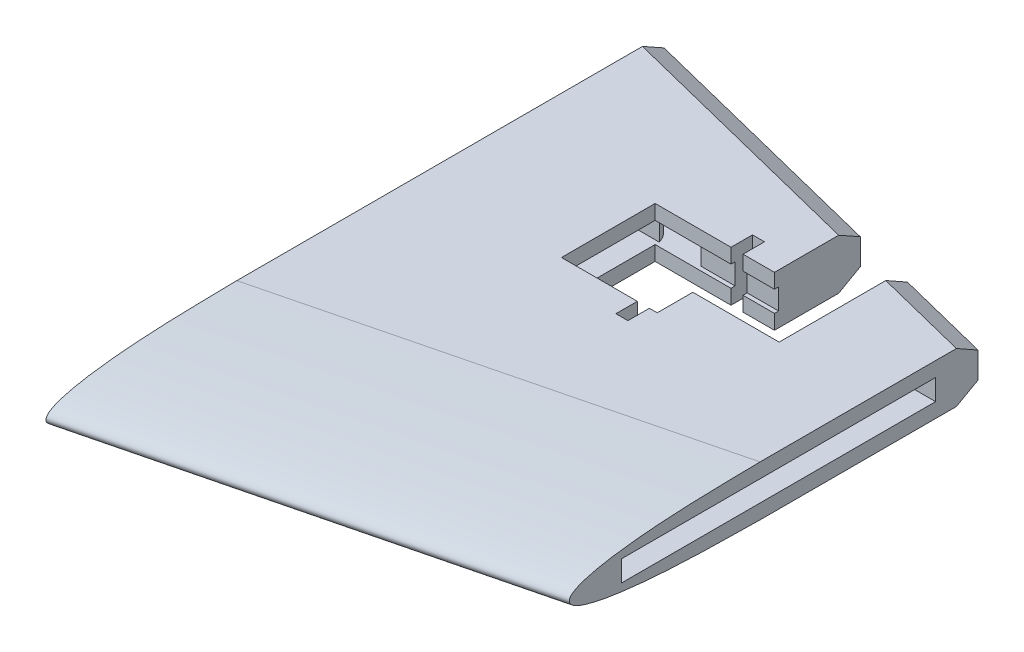
SolidWorks part; units mm, degrees
material "ABS"
ref_plane "Front Plane" through (0, 0, 0) normal (0, 0, 1) x (1, 0, 0)
ref_plane "Top Plane" through (0, 0, 0) normal (0, 1, 0) x (1, 0, 0)
ref_plane "Right Plane" through (0, 0, 0) normal (1, 0, 0) x (0, 0, -1)
sketch "Sketch2" plane through (0, 0, 0) normal (1, 0, 0) x (0, 0, -1)
  line L0 (10, -10.5) -> (10, 10.5)
  line L1 (20, -10.5) -> (20, 10.5)
  line L2 (30, -10.5) -> (30, 10.5)
  line L3 (40, -10.5) -> (40, 10.5)
  line L4 (50, -10.5) -> (50, 10.5)
  line L5 (60, -10.5) -> (60, 10.5)
  line L6 (70, -10.5) -> (70, 10.5)
  line L7 (80, -10.5) -> (80, 10.5)
  line L8 (90, -10.5) -> (90, 10.5)
  line L9 (100, -10.5) -> (100, 10.5)
  line L10 (110, -10.5) -> (110, 10.5)
  line L11 (120, -10.5) -> (120, 10.5)
  line L12 (130, -10.5) -> (130, 10.5)
  line L13 (140, -10.5) -> (140, 10.5)
  line L14 (150, -10.5) -> (150, 10.5)
  line L15 (-4.5, 10) -> (154.5, 10)
  line L16 (-4.5, -10) -> (154.5, -10)
  line L17 (150, 0.13) -> (149.77, 0.15)
  line L18 (149.77, 0.15) -> (149.08, 0.21)
  line L19 (149.08, 0.21) -> (147.93, 0.32)
  line L20 (147.93, 0.32) -> (146.33, 0.46)
  line L21 (146.33, 0.46) -> (144.29, 0.65)
  line L22 (144.29, 0.65) -> (141.83, 0.87)
  line L23 (141.83, 0.87) -> (138.95, 1.11)
  line L24 (138.95, 1.11) -> (135.68, 1.39)
  line L25 (135.68, 1.39) -> (132.03, 1.69)
  line L26 (132.03, 1.69) -> (128.03, 2.01)
  line L27 (128.03, 2.01) -> (123.71, 2.35)
  line L28 (123.71, 2.35) -> (119.08, 2.69)
  line L29 (119.08, 2.69) -> (114.19, 3.04)
  line L30 (114.19, 3.04) -> (109.05, 3.4)
  line L31 (109.05, 3.4) -> (103.7, 3.75)
  line L32 (103.7, 3.75) -> (98.18, 4.09)
  line L33 (98.18, 4.09) -> (92.51, 4.42)
  line L34 (92.51, 4.42) -> (86.73, 4.74)
  line L35 (86.73, 4.74) -> (80.88, 5.03)
  line L36 (80.88, 5.03) -> (75, 5.29)
  line L37 (75, 5.29) -> (69.12, 5.52)
  line L38 (69.12, 5.52) -> (63.27, 5.71)
  line L39 (63.27, 5.71) -> (57.49, 5.86)
  line L40 (57.49, 5.86) -> (51.82, 5.96)
  line L41 (51.82, 5.96) -> (46.3, 6)
  line L42 (46.3, 6) -> (40.95, 5.98)
  line L43 (40.95, 5.98) -> (35.81, 5.91)
  line L44 (35.81, 5.91) -> (30.92, 5.77)
  line L45 (30.92, 5.77) -> (26.29, 5.57)
  line L46 (26.29, 5.57) -> (21.97, 5.31)
  line L47 (21.97, 5.31) -> (17.97, 4.99)
  line L48 (17.97, 4.99) -> (14.32, 4.6)
  line L49 (14.32, 4.6) -> (11.05, 4.17)
  line L50 (11.05, 4.17) -> (8.17, 3.69)
  line L51 (8.17, 3.69) -> (5.71, 3.16)
  line L52 (5.71, 3.16) -> (3.67, 2.59)
  line L53 (3.67, 2.59) -> (2.07, 1.99)
  line L54 (2.07, 1.99) -> (0.92, 1.35)
  line L55 (0.92, 1.35) -> (0.23, 0.69)
  line L56 (0.23, 0.69) -> (0, 0)
  line L57 (0, 0) -> (0.23, -0.69)
  line L58 (0.23, -0.69) -> (0.92, -1.35)
  line L59 (0.92, -1.35) -> (2.07, -1.99)
  line L60 (2.07, -1.99) -> (3.67, -2.59)
  line L61 (3.67, -2.59) -> (5.71, -3.16)
  line L62 (5.71, -3.16) -> (8.17, -3.69)
  line L63 (8.17, -3.69) -> (11.05, -4.17)
  line L64 (11.05, -4.17) -> (14.32, -4.6)
  line L65 (14.32, -4.6) -> (17.97, -4.99)
  line L66 (17.97, -4.99) -> (21.97, -5.31)
  line L67 (21.97, -5.31) -> (26.29, -5.57)
  line L68 (26.29, -5.57) -> (30.92, -5.77)
  line L69 (30.92, -5.77) -> (35.81, -5.91)
  line L70 (35.81, -5.91) -> (40.95, -5.98)
  line L71 (40.95, -5.98) -> (46.3, -6)
  line L72 (46.3, -6) -> (51.82, -5.96)
  line L73 (51.82, -5.96) -> (57.49, -5.86)
  line L74 (57.49, -5.86) -> (63.27, -5.71)
  line L75 (63.27, -5.71) -> (69.12, -5.52)
  line L76 (69.12, -5.52) -> (75, -5.29)
  line L77 (75, -5.29) -> (80.88, -5.03)
  line L78 (80.88, -5.03) -> (86.73, -4.74)
  line L79 (86.73, -4.74) -> (92.51, -4.42)
  line L80 (92.51, -4.42) -> (98.18, -4.09)
  line L81 (98.18, -4.09) -> (103.7, -3.75)
  line L82 (103.7, -3.75) -> (109.05, -3.4)
  line L83 (109.05, -3.4) -> (114.19, -3.04)
  line L84 (114.19, -3.04) -> (119.08, -2.69)
  line L85 (119.08, -2.69) -> (123.71, -2.35)
  line L86 (123.71, -2.35) -> (128.03, -2.01)
  line L87 (128.03, -2.01) -> (132.03, -1.69)
  line L88 (132.03, -1.69) -> (135.68, -1.39)
  line L89 (135.68, -1.39) -> (138.95, -1.11)
  line L90 (138.95, -1.11) -> (141.83, -0.87)
  line L91 (141.83, -0.87) -> (144.29, -0.65)
  line L92 (144.29, -0.65) -> (146.33, -0.46)
  line L93 (146.33, -0.46) -> (147.93, -0.32)
  line L94 (147.93, -0.32) -> (149.08, -0.21)
  line L95 (149.08, -0.21) -> (149.77, -0.15)
  line L96 (149.77, -0.15) -> (150, -0.13)
  line L97 (0, 0) -> (150, 0)
  line L98 (-4.5, 0) -> (154.5, 0)
  line L99 (0, -10.5) -> (0, 10.5)
  line L100 (-2.7943, -13.5) -> (-2.7943, -11.5673)
  line L101 (-2.7943, -11.5673) -> (-2.532, -11.5673)
  line L102 (-2.532, -11.5673) -> (-1.5168, -13.0847)
  line L103 (-1.5168, -13.0847) -> (-1.5168, -11.5673)
  line L104 (-1.5168, -11.5673) -> (-1.2716, -11.5673)
  line L105 (-1.2716, -11.5673) -> (-1.2716, -13.5)
  line L106 (-1.2716, -13.5) -> (-1.534, -13.5)
  line L107 (-1.534, -13.5) -> (-2.5491, -11.9812)
  line L108 (-2.5491, -11.9812) -> (-2.5491, -13.5)
  line L109 (-2.5491, -13.5) -> (-2.7943, -13.5)
  line L110 (0.0415, -13.3273) -> (-0.213, -13.4855)
  line L111 (-0.213, -13.4855) -> (-0.474, -13.5316)
  line L112 (-0.474, -13.5316) -> (-0.8287, -13.4196)
  line L113 (-0.8287, -13.4196) -> (-0.9526, -13.1309)
  line L114 (-0.9526, -13.1309) -> (-0.9064, -12.9437)
  line L115 (-0.9064, -12.9437) -> (-0.7838, -12.8065)
  line L116 (-0.7838, -12.8065) -> (-0.6125, -12.7288)
  line L117 (-0.6125, -12.7288) -> (-0.4015, -12.6932)
  line L118 (-0.4015, -12.6932) -> (0.0217, -12.6114)
  line L119 (0.0217, -12.6114) -> (0.023, -12.5495)
  line L120 (0.023, -12.5495) -> (-0.0442, -12.3451)
  line L121 (-0.0442, -12.3451) -> (-0.3145, -12.2647)
  line L122 (-0.3145, -12.2647) -> (-0.5624, -12.324)
  line L123 (-0.5624, -12.324) -> (-0.6797, -12.531)
  line L124 (-0.6797, -12.531) -> (-0.9117, -12.4994)
  line L125 (-0.9117, -12.4994) -> (-0.8076, -12.2594)
  line L126 (-0.8076, -12.2594) -> (-0.5979, -12.1184)
  line L127 (-0.5979, -12.1184) -> (-0.2802, -12.0683)
  line L128 (-0.2802, -12.0683) -> (0.0111, -12.1104)
  line L129 (0.0111, -12.1104) -> (0.1759, -12.2172)
  line L130 (0.1759, -12.2172) -> (0.2498, -12.3781)
  line L131 (0.2498, -12.3781) -> (0.2616, -12.5969)
  line L132 (0.2616, -12.5969) -> (0.2616, -12.9133)
  line L133 (0.2616, -12.9133) -> (0.2761, -13.3326)
  line L134 (0.2761, -13.3326) -> (0.3368, -13.5)
  line L135 (0.3368, -13.5) -> (0.0889, -13.5)
  line L136 (0.0889, -13.5) -> (0.0415, -13.3273)
  line L137 (0.0217, -12.7973) -> (-0.3659, -12.887)
  line L138 (-0.3659, -12.887) -> (-0.5729, -12.9344)
  line L139 (-0.5729, -12.9344) -> (-0.6665, -13.0122)
  line L140 (-0.6665, -13.0122) -> (-0.6995, -13.1243)
  line L141 (-0.6995, -13.1243) -> (-0.6283, -13.2825)
  line L142 (-0.6283, -13.2825) -> (-0.4173, -13.3458)
  line L143 (-0.4173, -13.3458) -> (-0.1734, -13.2864)
  line L144 (-0.1734, -13.2864) -> (-0.0166, -13.1216)
  line L145 (-0.0166, -13.1216) -> (0.0217, -12.8843)
  line L146 (0.0217, -12.8843) -> (0.0217, -12.7973)
  line L147 (0.6294, -13.5) -> (0.6294, -12.0999)
  line L148 (0.6294, -12.0999) -> (0.8417, -12.0999)
  line L149 (0.8417, -12.0999) -> (0.8417, -12.2963)
  line L150 (0.8417, -12.2963) -> (1.017, -12.1315)
  line L151 (1.017, -12.1315) -> (1.2662, -12.0683)
  line L152 (1.2662, -12.0683) -> (1.5207, -12.1329)
  line L153 (1.5207, -12.1329) -> (1.6617, -12.3135)
  line L154 (1.6617, -12.3135) -> (2.0941, -12.0683)
  line L155 (2.0941, -12.0683) -> (2.4145, -12.1843)
  line L156 (2.4145, -12.1843) -> (2.5266, -12.5389)
  line L157 (2.5266, -12.5389) -> (2.5266, -13.5)
  line L158 (2.5266, -13.5) -> (2.2906, -13.5)
  line L159 (2.2906, -13.5) -> (2.2906, -12.618)
  line L160 (2.2906, -12.618) -> (2.2668, -12.4137)
  line L161 (2.2668, -12.4137) -> (2.1838, -12.3122)
  line L162 (2.1838, -12.3122) -> (2.0414, -12.2739)
  line L163 (2.0414, -12.2739) -> (1.7962, -12.3728)
  line L164 (1.7962, -12.3728) -> (1.6986, -12.6866)
  line L165 (1.6986, -12.6866) -> (1.6986, -13.5)
  line L166 (1.6986, -13.5) -> (1.4613, -13.5)
  line L167 (1.4613, -13.5) -> (1.4613, -12.5903)
  line L168 (1.4613, -12.5903) -> (1.4033, -12.353)
  line L169 (1.4033, -12.353) -> (1.2135, -12.2739)
  line L170 (1.2135, -12.2739) -> (1.0276, -12.3267)
  line L171 (1.0276, -12.3267) -> (0.905, -12.4809)
  line L172 (0.905, -12.4809) -> (0.8667, -12.7736)
  line L173 (0.8667, -12.7736) -> (0.8667, -13.5)
  line L174 (0.8667, -13.5) -> (0.6294, -13.5)
  line L175 (3.837, -13.0491) -> (4.0822, -13.0794)
  line L176 (4.0822, -13.0794) -> (3.8673, -13.413)
  line L177 (3.8673, -13.413) -> (3.4666, -13.5316)
  line L178 (3.4666, -13.5316) -> (2.9788, -13.3431)
  line L179 (2.9788, -13.3431) -> (2.7995, -12.8118)
  line L180 (2.7995, -12.8118) -> (2.9814, -12.2634)
  line L181 (2.9814, -12.2634) -> (3.4534, -12.0683)
  line L182 (3.4534, -12.0683) -> (3.9122, -12.2594)
  line L183 (3.9122, -12.2594) -> (4.0901, -12.7973)
  line L184 (4.0901, -12.7973) -> (4.0888, -12.8606)
  line L185 (4.0888, -12.8606) -> (3.0447, -12.8606)
  line L186 (3.0447, -12.8606) -> (3.1752, -13.2139)
  line L187 (3.1752, -13.2139) -> (3.4679, -13.3365)
  line L188 (3.4679, -13.3365) -> (3.6907, -13.268)
  line L189 (3.6907, -13.268) -> (3.837, -13.0491)
  line L190 (3.0579, -12.6655) -> (3.8396, -12.6655)
  line L191 (3.8396, -12.6655) -> (3.75, -12.4005)
  line L192 (3.75, -12.4005) -> (3.456, -12.2634)
  line L193 (3.456, -12.2634) -> (3.1805, -12.3728)
  line L194 (3.1805, -12.3728) -> (3.0579, -12.6655)
  line L195 (6.3788, -12.3636) -> (5.1026, -12.3636)
  line L196 (5.1026, -12.3636) -> (5.1026, -12.1421)
  line L197 (5.1026, -12.1421) -> (6.3788, -12.1421)
  line L198 (6.3788, -12.1421) -> (6.3788, -12.3636)
  line L199 (6.3788, -12.9502) -> (5.1026, -12.9502)
  line L200 (5.1026, -12.9502) -> (5.1026, -12.7288)
  line L201 (5.1026, -12.7288) -> (6.3788, -12.7288)
  line L202 (6.3788, -12.7288) -> (6.3788, -12.9502)
  line L203 (7.4849, -13.5) -> (7.4849, -11.5673)
  line L204 (7.4849, -11.5673) -> (7.7473, -11.5673)
  line L205 (7.7473, -11.5673) -> (8.7624, -13.0847)
  line L206 (8.7624, -13.0847) -> (8.7624, -11.5673)
  line L207 (8.7624, -11.5673) -> (9.0076, -11.5673)
  line L208 (9.0076, -11.5673) -> (9.0076, -13.5)
  line L209 (9.0076, -13.5) -> (8.7453, -13.5)
  line L210 (8.7453, -13.5) -> (7.7301, -11.9812)
  line L211 (7.7301, -11.9812) -> (7.7301, -13.5)
  line L212 (7.7301, -13.5) -> (7.4849, -13.5)
  line L213 (9.2251, -13.5) -> (9.9674, -11.5673)
  line L214 (9.9674, -11.5673) -> (10.2429, -11.5673)
  line L215 (10.2429, -11.5673) -> (11.0339, -13.5)
  line L216 (11.0339, -13.5) -> (10.7426, -13.5)
  line L217 (10.7426, -13.5) -> (10.5171, -12.9146)
  line L218 (10.5171, -12.9146) -> (9.709, -12.9146)
  line L219 (9.709, -12.9146) -> (9.4967, -13.5)
  line L220 (9.4967, -13.5) -> (9.2251, -13.5)
  line L221 (9.7828, -12.7063) -> (10.438, -12.7063)
  line L222 (10.438, -12.7063) -> (10.2363, -12.1711)
  line L223 (10.2363, -12.1711) -> (10.0992, -11.7703)
  line L224 (10.0992, -11.7703) -> (9.9951, -12.1395)
  line L225 (9.9951, -12.1395) -> (9.7828, -12.7063)
  line L226 (12.6173, -12.8224) -> (12.873, -12.887)
  line L227 (12.873, -12.887) -> (12.583, -13.3682)
  line L228 (12.583, -13.3682) -> (12.0728, -13.533)
  line L229 (12.0728, -13.533) -> (11.5639, -13.4064)
  line L230 (11.5639, -13.4064) -> (11.266, -13.0373)
  line L231 (11.266, -13.0373) -> (11.1645, -12.5191)
  line L232 (11.1645, -12.5191) -> (11.2792, -11.9931)
  line L233 (11.2792, -11.9931) -> (11.6074, -11.6517)
  line L234 (11.6074, -11.6517) -> (12.0768, -11.5343)
  line L235 (12.0768, -11.5343) -> (12.5646, -11.682)
  line L236 (12.5646, -11.682) -> (12.8401, -12.0973)
  line L237 (12.8401, -12.0973) -> (12.5883, -12.1566)
  line L238 (12.5883, -12.1566) -> (12.3932, -11.8494)
  line L239 (12.3932, -11.8494) -> (12.0715, -11.7532)
  line L240 (12.0715, -11.7532) -> (11.6984, -11.86)
  line L241 (11.6984, -11.86) -> (11.4888, -12.1474)
  line L242 (11.4888, -12.1474) -> (11.4281, -12.5178)
  line L243 (11.4281, -12.5178) -> (11.4993, -12.9489)
  line L244 (11.4993, -12.9489) -> (11.7234, -13.2231)
  line L245 (11.7234, -13.2231) -> (12.0517, -13.3141)
  line L246 (12.0517, -13.3141) -> (12.4156, -13.1902)
  line L247 (12.4156, -13.1902) -> (12.6173, -12.8224)
  line L248 (12.9759, -13.5) -> (13.7181, -11.5673)
  line L249 (13.7181, -11.5673) -> (13.9937, -11.5673)
  line L250 (13.9937, -11.5673) -> (14.7847, -13.5)
  line L251 (14.7847, -13.5) -> (14.4933, -13.5)
  line L252 (14.4933, -13.5) -> (14.2679, -12.9146)
  line L253 (14.2679, -12.9146) -> (13.4597, -12.9146)
  line L254 (13.4597, -12.9146) -> (13.2475, -13.5)
  line L255 (13.2475, -13.5) -> (12.9759, -13.5)
  line L256 (13.5335, -12.7063) -> (14.1888, -12.7063)
  line L257 (14.1888, -12.7063) -> (13.9871, -12.1711)
  line L258 (13.9871, -12.1711) -> (13.8499, -11.7703)
  line L259 (13.8499, -11.7703) -> (13.7458, -12.1395)
  line L260 (13.7458, -12.1395) -> (13.5335, -12.7063)
  line L261 (15.4939, -12.5468) -> (15.5638, -11.9958)
  line L262 (15.5638, -11.9958) -> (15.7734, -11.6728)
  line L263 (15.7734, -11.6728) -> (16.1241, -11.5594)
  line L264 (16.1241, -11.5594) -> (16.397, -11.6227)
  line L265 (16.397, -11.6227) -> (16.5908, -11.8033)
  line L266 (16.5908, -11.8033) -> (16.7108, -12.0907)
  line L267 (16.7108, -12.0907) -> (16.7543, -12.5468)
  line L268 (16.7543, -12.5468) -> (16.6844, -13.0966)
  line L269 (16.6844, -13.0966) -> (16.4748, -13.4196)
  line L270 (16.4748, -13.4196) -> (16.1241, -13.533)
  line L271 (16.1241, -13.533) -> (15.6851, -13.3326)
  line L272 (15.6851, -13.3326) -> (15.4939, -12.5468)
  line L273 (15.7378, -12.5468) -> (15.8486, -13.181)
  line L274 (15.8486, -13.181) -> (16.1241, -13.3378)
  line L275 (16.1241, -13.3378) -> (16.3983, -13.1796)
  line L276 (16.3983, -13.1796) -> (16.5104, -12.5468)
  line L277 (16.5104, -12.5468) -> (16.3983, -11.9127)
  line L278 (16.3983, -11.9127) -> (16.1215, -11.7558)
  line L279 (16.1215, -11.7558) -> (15.8605, -11.8942)
  line L280 (15.8605, -11.8942) -> (15.7378, -12.5468)
  line L281 (16.9956, -12.5468) -> (17.0654, -11.9958)
  line L282 (17.0654, -11.9958) -> (17.275, -11.6728)
  line L283 (17.275, -11.6728) -> (17.6257, -11.5594)
  line L284 (17.6257, -11.5594) -> (17.8986, -11.6227)
  line L285 (17.8986, -11.6227) -> (18.0924, -11.8033)
  line L286 (18.0924, -11.8033) -> (18.2124, -12.0907)
  line L287 (18.2124, -12.0907) -> (18.2559, -12.5468)
  line L288 (18.2559, -12.5468) -> (18.186, -13.0966)
  line L289 (18.186, -13.0966) -> (17.9764, -13.4196)
  line L290 (17.9764, -13.4196) -> (17.6257, -13.533)
  line L291 (17.6257, -13.533) -> (17.1867, -13.3326)
  line L292 (17.1867, -13.3326) -> (16.9956, -12.5468)
  line L293 (17.2395, -12.5468) -> (17.3502, -13.181)
  line L294 (17.3502, -13.181) -> (17.6257, -13.3378)
  line L295 (17.6257, -13.3378) -> (17.9, -13.1796)
  line L296 (17.9, -13.1796) -> (18.012, -12.5468)
  line L297 (18.012, -12.5468) -> (17.9, -11.9127)
  line L298 (17.9, -11.9127) -> (17.6231, -11.7558)
  line L299 (17.6231, -11.7558) -> (17.3621, -11.8942)
  line L300 (17.3621, -11.8942) -> (17.2395, -12.5468)
  line L301 (18.4972, -12.5468) -> (18.567, -11.9958)
  line L302 (18.567, -11.9958) -> (18.7767, -11.6728)
  line L303 (18.7767, -11.6728) -> (19.1273, -11.5594)
  line L304 (19.1273, -11.5594) -> (19.4002, -11.6227)
  line L305 (19.4002, -11.6227) -> (19.594, -11.8033)
  line L306 (19.594, -11.8033) -> (19.714, -12.0907)
  line L307 (19.714, -12.0907) -> (19.7575, -12.5468)
  line L308 (19.7575, -12.5468) -> (19.6876, -13.0966)
  line L309 (19.6876, -13.0966) -> (19.478, -13.4196)
  line L310 (19.478, -13.4196) -> (19.1273, -13.533)
  line L311 (19.1273, -13.533) -> (18.6883, -13.3326)
  line L312 (18.6883, -13.3326) -> (18.4972, -12.5468)
  line L313 (18.7411, -12.5468) -> (18.8518, -13.181)
  line L314 (18.8518, -13.181) -> (19.1273, -13.3378)
  line L315 (19.1273, -13.3378) -> (19.4016, -13.1796)
  line L316 (19.4016, -13.1796) -> (19.5136, -12.5468)
  line L317 (19.5136, -12.5468) -> (19.4016, -11.9127)
  line L318 (19.4016, -11.9127) -> (19.1247, -11.7558)
  line L319 (19.1247, -11.7558) -> (18.8637, -11.8942)
  line L320 (18.8637, -11.8942) -> (18.7411, -12.5468)
  line L321 (20.364, -12.4519) -> (20.1451, -12.2977)
  line L322 (20.1451, -12.2977) -> (20.0739, -12.0577)
  line L323 (20.0739, -12.0577) -> (20.2255, -11.7031)
  line L324 (20.2255, -11.7031) -> (20.629, -11.5594)
  line L325 (20.629, -11.5594) -> (21.0363, -11.707)
  line L326 (21.0363, -11.707) -> (21.1906, -12.0643)
  line L327 (21.1906, -12.0643) -> (21.1194, -12.299)
  line L328 (21.1194, -12.299) -> (20.9058, -12.4519)
  line L329 (20.9058, -12.4519) -> (21.1761, -12.6391)
  line L330 (21.1761, -12.6391) -> (21.2697, -12.9476)
  line L331 (21.2697, -12.9476) -> (21.0943, -13.3642)
  line L332 (21.0943, -13.3642) -> (20.6329, -13.533)
  line L333 (20.6329, -13.533) -> (20.1715, -13.3642)
  line L334 (20.1715, -13.3642) -> (19.9961, -12.941)
  line L335 (19.9961, -12.941) -> (20.0911, -12.6259)
  line L336 (20.0911, -12.6259) -> (20.364, -12.4519)
  line L337 (20.3165, -12.0498) -> (20.4048, -12.2739)
  line L338 (20.4048, -12.2739) -> (20.6342, -12.3609)
  line L339 (20.6342, -12.3609) -> (20.8584, -12.2752)
  line L340 (20.8584, -12.2752) -> (20.9467, -12.063)
  line L341 (20.9467, -12.063) -> (20.8557, -11.8441)
  line L342 (20.8557, -11.8441) -> (20.6316, -11.7545)
  line L343 (20.6316, -11.7545) -> (20.4062, -11.8415)
  line L344 (20.4062, -11.8415) -> (20.3165, -12.0498)
  line L345 (20.24, -12.9423) -> (20.2875, -13.1388)
  line L346 (20.2875, -13.1388) -> (20.4312, -13.2864)
  line L347 (20.4312, -13.2864) -> (20.6355, -13.3378)
  line L348 (20.6355, -13.3378) -> (20.9164, -13.2284)
  line L349 (20.9164, -13.2284) -> (21.0271, -12.9502)
  line L350 (21.0271, -12.9502) -> (20.9124, -12.6668)
  line L351 (20.9124, -12.6668) -> (20.6276, -12.5547)
  line L352 (20.6276, -12.5547) -> (20.3495, -12.6655)
  line L353 (20.3495, -12.6655) -> (20.24, -12.9423)
  line L354 (21.9855, -13.5) -> (22.7278, -11.5673)
  line L355 (22.7278, -11.5673) -> (23.0033, -11.5673)
  line L356 (23.0033, -11.5673) -> (23.7943, -13.5)
  line L357 (23.7943, -13.5) -> (23.503, -13.5)
  line L358 (23.503, -13.5) -> (23.2775, -12.9146)
  line L359 (23.2775, -12.9146) -> (22.4694, -12.9146)
  line L360 (22.4694, -12.9146) -> (22.2571, -13.5)
  line L361 (22.2571, -13.5) -> (21.9855, -13.5)
  line L362 (22.5432, -12.7063) -> (23.1984, -12.7063)
  line L363 (23.1984, -12.7063) -> (22.9967, -12.1711)
  line L364 (22.9967, -12.1711) -> (22.8596, -11.7703)
  line L365 (22.8596, -11.7703) -> (22.7555, -12.1395)
  line L366 (22.7555, -12.1395) -> (22.5432, -12.7063)
  line L367 (23.9697, -11.8402) -> (23.9697, -11.5673)
  line L368 (23.9697, -11.5673) -> (24.207, -11.5673)
  line L369 (24.207, -11.5673) -> (24.207, -11.8402)
  line L370 (24.207, -11.8402) -> (23.9697, -11.8402)
  line L371 (23.9697, -13.5) -> (23.9697, -12.0999)
  line L372 (23.9697, -12.0999) -> (24.207, -12.0999)
  line L373 (24.207, -12.0999) -> (24.207, -13.5)
  line L374 (24.207, -13.5) -> (23.9697, -13.5)
  line L375 (24.5656, -13.5) -> (24.5656, -12.0999)
  line L376 (24.5656, -12.0999) -> (24.7792, -12.0999)
  line L377 (24.7792, -12.0999) -> (24.7792, -12.3122)
  line L378 (24.7792, -12.3122) -> (24.9294, -12.1157)
  line L379 (24.9294, -12.1157) -> (25.0824, -12.0683)
  line L380 (25.0824, -12.0683) -> (25.3263, -12.1447)
  line L381 (25.3263, -12.1447) -> (25.2445, -12.3649)
  line L382 (25.2445, -12.3649) -> (25.0705, -12.3135)
  line L383 (25.0705, -12.3135) -> (24.9308, -12.3609)
  line L384 (24.9308, -12.3609) -> (24.8424, -12.4901)
  line L385 (24.8424, -12.4901) -> (24.8029, -12.767)
  line L386 (24.8029, -12.767) -> (24.8029, -13.5)
  line L387 (24.8029, -13.5) -> (24.5656, -13.5)
  line L388 (25.524, -13.5) -> (25.524, -12.2845)
  line L389 (25.524, -12.2845) -> (25.3144, -12.2845)
  line L390 (25.3144, -12.2845) -> (25.3144, -12.0999)
  line L391 (25.3144, -12.0999) -> (25.524, -12.0999)
  line L392 (25.524, -12.0999) -> (25.524, -11.9509)
  line L393 (25.524, -11.9509) -> (25.5491, -11.7413)
  line L394 (25.5491, -11.7413) -> (25.669, -11.5923)
  line L395 (25.669, -11.5923) -> (25.9116, -11.5343)
  line L396 (25.9116, -11.5343) -> (26.1331, -11.5581)
  line L397 (26.1331, -11.5581) -> (26.0975, -11.765)
  line L398 (26.0975, -11.765) -> (25.9578, -11.7519)
  line L399 (25.9578, -11.7519) -> (25.8048, -11.798)
  line L400 (25.8048, -11.798) -> (25.76, -11.9707)
  line L401 (25.76, -11.9707) -> (25.76, -12.0999)
  line L402 (25.76, -12.0999) -> (26.0329, -12.0999)
  line L403 (26.0329, -12.0999) -> (26.0329, -12.2845)
  line L404 (26.0329, -12.2845) -> (25.76, -12.2845)
  line L405 (25.76, -12.2845) -> (25.76, -13.5)
  line L406 (25.76, -13.5) -> (25.524, -13.5)
  line L407 (26.1291, -12.8) -> (26.3454, -12.2238)
  line L408 (26.3454, -12.2238) -> (26.7857, -12.0683)
  line L409 (26.7857, -12.0683) -> (27.2577, -12.2581)
  line L410 (27.2577, -12.2581) -> (27.4409, -12.7802)
  line L411 (27.4409, -12.7802) -> (27.3592, -13.206)
  line L412 (27.3592, -13.206) -> (27.1232, -13.4459)
  line L413 (27.1232, -13.4459) -> (26.7857, -13.5316)
  line L414 (26.7857, -13.5316) -> (26.3098, -13.3431)
  line L415 (26.3098, -13.3431) -> (26.1291, -12.8)
  line L416 (26.373, -12.8) -> (26.4904, -13.2034)
  line L417 (26.4904, -13.2034) -> (26.7857, -13.3365)
  line L418 (26.7857, -13.3365) -> (27.0797, -13.2021)
  line L419 (27.0797, -13.2021) -> (27.197, -12.792)
  line L420 (27.197, -12.792) -> (27.0784, -12.3992)
  line L421 (27.0784, -12.3992) -> (26.7857, -12.2647)
  line L422 (26.7857, -12.2647) -> (26.4904, -12.3979)
  line L423 (26.4904, -12.3979) -> (26.373, -12.8)
  line L424 (27.7204, -11.8402) -> (27.7204, -11.5673)
  line L425 (27.7204, -11.5673) -> (27.9577, -11.5673)
  line L426 (27.9577, -11.5673) -> (27.9577, -11.8402)
  line L427 (27.9577, -11.8402) -> (27.7204, -11.8402)
  line L428 (27.7204, -13.5) -> (27.7204, -12.0999)
  line L429 (27.7204, -12.0999) -> (27.9577, -12.0999)
  line L430 (27.9577, -12.0999) -> (27.9577, -13.5)
  line L431 (27.9577, -13.5) -> (27.7204, -13.5)
  line L432 (28.3137, -13.5) -> (28.3137, -11.5673)
  line L433 (28.3137, -11.5673) -> (28.551, -11.5673)
  line L434 (28.551, -11.5673) -> (28.551, -13.5)
  line L435 (28.551, -13.5) -> (28.3137, -13.5)
  line L436 (29.6914, -13.5) -> (29.6914, -11.5673)
  line L437 (29.6914, -11.5673) -> (30.0763, -11.5673)
  line L438 (30.0763, -11.5673) -> (30.5338, -12.9357)
  line L439 (30.5338, -12.9357) -> (30.6261, -13.2218)
  line L440 (30.6261, -13.2218) -> (30.7289, -12.912)
  line L441 (30.7289, -12.912) -> (31.1916, -11.5673)
  line L442 (31.1916, -11.5673) -> (31.5357, -11.5673)
  line L443 (31.5357, -11.5673) -> (31.5357, -13.5)
  line L444 (31.5357, -13.5) -> (31.2892, -13.5)
  line L445 (31.2892, -13.5) -> (31.2892, -11.8824)
  line L446 (31.2892, -11.8824) -> (30.7276, -13.5)
  line L447 (30.7276, -13.5) -> (30.4969, -13.5)
  line L448 (30.4969, -13.5) -> (29.9379, -11.8547)
  line L449 (29.9379, -11.8547) -> (29.9379, -13.5)
  line L450 (29.9379, -13.5) -> (29.6914, -13.5)
  line L451 (33.1666, -12.3636) -> (31.8904, -12.3636)
  line L452 (31.8904, -12.3636) -> (31.8904, -12.1421)
  line L453 (31.8904, -12.1421) -> (33.1666, -12.1421)
  line L454 (33.1666, -12.1421) -> (33.1666, -12.3636)
  line L455 (33.1666, -12.9502) -> (31.8904, -12.9502)
  line L456 (31.8904, -12.9502) -> (31.8904, -12.7288)
  line L457 (31.8904, -12.7288) -> (33.1666, -12.7288)
  line L458 (33.1666, -12.7288) -> (33.1666, -12.9502)
  line L459 (33.4289, -12.5468) -> (33.4988, -11.9958)
  line L460 (33.4988, -11.9958) -> (33.7084, -11.6728)
  line L461 (33.7084, -11.6728) -> (34.0591, -11.5594)
  line L462 (34.0591, -11.5594) -> (34.332, -11.6227)
  line L463 (34.332, -11.6227) -> (34.5258, -11.8033)
  line L464 (34.5258, -11.8033) -> (34.6457, -12.0907)
  line L465 (34.6457, -12.0907) -> (34.6892, -12.5468)
  line L466 (34.6892, -12.5468) -> (34.6194, -13.0966)
  line L467 (34.6194, -13.0966) -> (34.4098, -13.4196)
  line L468 (34.4098, -13.4196) -> (34.0591, -13.533)
  line L469 (34.0591, -13.533) -> (33.6201, -13.3326)
  line L470 (33.6201, -13.3326) -> (33.4289, -12.5468)
  line L471 (33.6728, -12.5468) -> (33.7835, -13.181)
  line L472 (33.7835, -13.181) -> (34.0591, -13.3378)
  line L473 (34.0591, -13.3378) -> (34.3333, -13.1796)
  line L474 (34.3333, -13.1796) -> (34.4454, -12.5468)
  line L475 (34.4454, -12.5468) -> (34.3333, -11.9127)
  line L476 (34.3333, -11.9127) -> (34.0564, -11.7558)
  line L477 (34.0564, -11.7558) -> (33.7954, -11.8942)
  line L478 (33.7954, -11.8942) -> (33.6728, -12.5468)
  line L479 (35.0637, -13.5) -> (35.0637, -13.2297)
  line L480 (35.0637, -13.2297) -> (35.3339, -13.2297)
  line L481 (35.3339, -13.2297) -> (35.3339, -13.5)
  line L482 (35.3339, -13.5) -> (35.0637, -13.5)
  line L483 (35.6807, -12.5468) -> (35.7505, -11.9958)
  line L484 (35.7505, -11.9958) -> (35.9602, -11.6728)
  line L485 (35.9602, -11.6728) -> (36.3108, -11.5594)
  line L486 (36.3108, -11.5594) -> (36.5837, -11.6227)
  line L487 (36.5837, -11.6227) -> (36.7775, -11.8033)
  line L488 (36.7775, -11.8033) -> (36.8975, -12.0907)
  line L489 (36.8975, -12.0907) -> (36.941, -12.5468)
  line L490 (36.941, -12.5468) -> (36.8711, -13.0966)
  line L491 (36.8711, -13.0966) -> (36.6615, -13.4196)
  line L492 (36.6615, -13.4196) -> (36.3108, -13.533)
  line L493 (36.3108, -13.533) -> (35.8718, -13.3326)
  line L494 (35.8718, -13.3326) -> (35.6807, -12.5468)
  line L495 (35.9246, -12.5468) -> (36.0353, -13.181)
  line L496 (36.0353, -13.181) -> (36.3108, -13.3378)
  line L497 (36.3108, -13.3378) -> (36.5851, -13.1796)
  line L498 (36.5851, -13.1796) -> (36.6971, -12.5468)
  line L499 (36.6971, -12.5468) -> (36.5851, -11.9127)
  line L500 (36.5851, -11.9127) -> (36.3082, -11.7558)
  line L501 (36.3082, -11.7558) -> (36.0472, -11.8942)
  line L502 (36.0472, -11.8942) -> (35.9246, -12.5468)
  line L503 (37.2271, -12.0313) -> (37.3312, -11.6793)
  line L504 (37.3312, -11.6793) -> (37.6331, -11.5343)
  line L505 (37.6331, -11.5343) -> (37.9337, -11.6648)
  line L506 (37.9337, -11.6648) -> (38.0537, -12.0458)
  line L507 (38.0537, -12.0458) -> (37.9324, -12.4242)
  line L508 (37.9324, -12.4242) -> (37.6358, -12.5561)
  line L509 (37.6358, -12.5561) -> (37.3431, -12.4255)
  line L510 (37.3431, -12.4255) -> (37.2271, -12.0313)
  line L511 (37.6397, -11.6978) -> (37.4921, -11.7743)
  line L512 (37.4921, -11.7743) -> (37.4341, -12.0551)
  line L513 (37.4341, -12.0551) -> (37.4934, -12.3174)
  line L514 (37.4934, -12.3174) -> (37.6397, -12.3926)
  line L515 (37.6397, -12.3926) -> (37.7874, -12.3161)
  line L516 (37.7874, -12.3161) -> (37.8467, -12.0366)
  line L517 (37.8467, -12.0366) -> (37.7874, -11.7743)
  line L518 (37.7874, -11.7743) -> (37.6397, -11.6978)
  line L519 (37.6411, -13.5712) -> (38.6984, -11.5343)
  line L520 (38.6984, -11.5343) -> (38.8909, -11.5343)
  line L521 (38.8909, -11.5343) -> (37.8375, -13.5712)
  line L522 (37.8375, -13.5712) -> (37.6411, -13.5712)
  line L523 (38.4769, -13.0465) -> (38.581, -12.6945)
  line L524 (38.581, -12.6945) -> (38.8843, -12.5495)
  line L525 (38.8843, -12.5495) -> (39.1849, -12.68)
  line L526 (39.1849, -12.68) -> (39.3048, -13.061)
  line L527 (39.3048, -13.061) -> (39.1835, -13.4394)
  line L528 (39.1835, -13.4394) -> (38.8856, -13.5712)
  line L529 (38.8856, -13.5712) -> (38.5929, -13.4407)
  line L530 (38.5929, -13.4407) -> (38.4769, -13.0465)
  line L531 (38.8909, -12.7129) -> (38.7419, -12.7894)
  line L532 (38.7419, -12.7894) -> (38.6839, -13.0702)
  line L533 (38.6839, -13.0702) -> (38.7432, -13.3312)
  line L534 (38.7432, -13.3312) -> (38.8895, -13.4077)
  line L535 (38.8895, -13.4077) -> (39.0385, -13.3312)
  line L536 (39.0385, -13.3312) -> (39.0979, -13.0518)
  line L537 (39.0979, -13.0518) -> (39.0385, -12.7894)
  line L538 (39.0385, -12.7894) -> (38.8909, -12.7129)
  line L539 (40.4294, -13.5) -> (40.4294, -11.5673)
  line L540 (40.4294, -11.5673) -> (41.1584, -11.5673)
  line L541 (41.1584, -11.5673) -> (41.4524, -11.5857)
  line L542 (41.4524, -11.5857) -> (41.6911, -11.6767)
  line L543 (41.6911, -11.6767) -> (41.8453, -11.8626)
  line L544 (41.8453, -11.8626) -> (41.9046, -12.1263)
  line L545 (41.9046, -12.1263) -> (41.7478, -12.5442)
  line L546 (41.7478, -12.5442) -> (41.1809, -12.7143)
  line L547 (41.1809, -12.7143) -> (40.6852, -12.7143)
  line L548 (40.6852, -12.7143) -> (40.6852, -13.5)
  line L549 (40.6852, -13.5) -> (40.4294, -13.5)
  line L550 (40.6852, -12.4862) -> (41.1848, -12.4862)
  line L551 (41.1848, -12.4862) -> (41.5368, -12.3939)
  line L552 (41.5368, -12.3939) -> (41.641, -12.1342)
  line L553 (41.641, -12.1342) -> (41.579, -11.9272)
  line L554 (41.579, -11.9272) -> (41.4182, -11.8125)
  line L555 (41.4182, -11.8125) -> (41.1795, -11.7954)
  line L556 (41.1795, -11.7954) -> (40.6851, -11.7954)
  line L557 (40.6851, -11.7954) -> (40.6852, -12.4862)
  line L558 (43.4484, -12.3636) -> (42.1723, -12.3636)
  line L559 (42.1723, -12.3636) -> (42.1723, -12.1421)
  line L560 (42.1723, -12.1421) -> (43.4484, -12.1421)
  line L561 (43.4484, -12.1421) -> (43.4484, -12.3636)
  line L562 (43.4484, -12.9502) -> (42.1723, -12.9502)
  line L563 (42.1723, -12.9502) -> (42.1723, -12.7288)
  line L564 (42.1723, -12.7288) -> (43.4484, -12.7288)
  line L565 (43.4484, -12.7288) -> (43.4484, -12.9502)
  line L566 (43.7108, -12.5468) -> (43.7807, -11.9958)
  line L567 (43.7807, -11.9958) -> (43.9903, -11.6728)
  line L568 (43.9903, -11.6728) -> (44.341, -11.5594)
  line L569 (44.341, -11.5594) -> (44.6139, -11.6227)
  line L570 (44.6139, -11.6227) -> (44.8077, -11.8033)
  line L571 (44.8077, -11.8033) -> (44.9276, -12.0907)
  line L572 (44.9276, -12.0907) -> (44.9711, -12.5468)
  line L573 (44.9711, -12.5468) -> (44.9013, -13.0966)
  line L574 (44.9013, -13.0966) -> (44.6916, -13.4196)
  line L575 (44.6916, -13.4196) -> (44.341, -13.533)
  line L576 (44.341, -13.533) -> (43.9019, -13.3326)
  line L577 (43.9019, -13.3326) -> (43.7108, -12.5468)
  line L578 (43.9547, -12.5468) -> (44.0654, -13.181)
  line L579 (44.0654, -13.181) -> (44.341, -13.3378)
  line L580 (44.341, -13.3378) -> (44.6152, -13.1796)
  line L581 (44.6152, -13.1796) -> (44.7272, -12.5468)
  line L582 (44.7272, -12.5468) -> (44.6152, -11.9127)
  line L583 (44.6152, -11.9127) -> (44.3383, -11.7558)
  line L584 (44.3383, -11.7558) -> (44.0773, -11.8942)
  line L585 (44.0773, -11.8942) -> (43.9547, -12.5468)
  line L586 (45.3456, -13.5) -> (45.3456, -13.2297)
  line L587 (45.3456, -13.2297) -> (45.6158, -13.2297)
  line L588 (45.6158, -13.2297) -> (45.6158, -13.5)
  line L589 (45.6158, -13.5) -> (45.3456, -13.5)
  line L590 (45.9625, -12.5468) -> (46.0324, -11.9958)
  line L591 (46.0324, -11.9958) -> (46.242, -11.6728)
  line L592 (46.242, -11.6728) -> (46.5927, -11.5594)
  line L593 (46.5927, -11.5594) -> (46.8656, -11.6227)
  line L594 (46.8656, -11.6227) -> (47.0594, -11.8033)
  line L595 (47.0594, -11.8033) -> (47.1794, -12.0907)
  line L596 (47.1794, -12.0907) -> (47.2229, -12.5468)
  line L597 (47.2229, -12.5468) -> (47.153, -13.0966)
  line L598 (47.153, -13.0966) -> (46.9434, -13.4196)
  line L599 (46.9434, -13.4196) -> (46.5927, -13.533)
  line L600 (46.5927, -13.533) -> (46.1537, -13.3326)
  line L601 (46.1537, -13.3326) -> (45.9625, -12.5468)
  line L602 (46.2064, -12.5468) -> (46.3172, -13.181)
  line L603 (46.3172, -13.181) -> (46.5927, -13.3378)
  line L604 (46.5927, -13.3378) -> (46.8669, -13.1796)
  line L605 (46.8669, -13.1796) -> (46.979, -12.5468)
  line L606 (46.979, -12.5468) -> (46.8669, -11.9127)
  line L607 (46.8669, -11.9127) -> (46.5901, -11.7558)
  line L608 (46.5901, -11.7558) -> (46.3291, -11.8942)
  line L609 (46.3291, -11.8942) -> (46.2064, -12.5468)
  line L610 (47.509, -12.0313) -> (47.6131, -11.6793)
  line L611 (47.6131, -11.6793) -> (47.915, -11.5343)
  line L612 (47.915, -11.5343) -> (48.2156, -11.6648)
  line L613 (48.2156, -11.6648) -> (48.3356, -12.0458)
  line L614 (48.3356, -12.0458) -> (48.2143, -12.4242)
  line L615 (48.2143, -12.4242) -> (47.9177, -12.5561)
  line L616 (47.9177, -12.5561) -> (47.625, -12.4255)
  line L617 (47.625, -12.4255) -> (47.509, -12.0313)
  line L618 (47.9216, -11.6978) -> (47.774, -11.7743)
  line L619 (47.774, -11.7743) -> (47.716, -12.0551)
  line L620 (47.716, -12.0551) -> (47.7753, -12.3174)
  line L621 (47.7753, -12.3174) -> (47.9216, -12.3926)
  line L622 (47.9216, -12.3926) -> (48.0693, -12.3161)
  line L623 (48.0693, -12.3161) -> (48.1286, -12.0366)
  line L624 (48.1286, -12.0366) -> (48.0693, -11.7743)
  line L625 (48.0693, -11.7743) -> (47.9216, -11.6978)
  line L626 (47.9229, -13.5712) -> (48.9803, -11.5343)
  line L627 (48.9803, -11.5343) -> (49.1728, -11.5343)
  line L628 (49.1728, -11.5343) -> (48.1194, -13.5712)
  line L629 (48.1194, -13.5712) -> (47.9229, -13.5712)
  line L630 (48.7588, -13.0465) -> (48.8629, -12.6945)
  line L631 (48.8629, -12.6945) -> (49.1662, -12.5495)
  line L632 (49.1662, -12.5495) -> (49.4667, -12.68)
  line L633 (49.4667, -12.68) -> (49.5867, -13.061)
  line L634 (49.5867, -13.061) -> (49.4654, -13.4394)
  line L635 (49.4654, -13.4394) -> (49.1675, -13.5712)
  line L636 (49.1675, -13.5712) -> (48.8748, -13.4407)
  line L637 (48.8748, -13.4407) -> (48.7588, -13.0465)
  line L638 (49.1728, -12.7129) -> (49.0238, -12.7894)
  line L639 (49.0238, -12.7894) -> (48.9658, -13.0702)
  line L640 (48.9658, -13.0702) -> (49.0251, -13.3312)
  line L641 (49.0251, -13.3312) -> (49.1714, -13.4077)
  line L642 (49.1714, -13.4077) -> (49.3204, -13.3312)
  line L643 (49.3204, -13.3312) -> (49.3797, -13.0518)
  line L644 (49.3797, -13.0518) -> (49.3204, -12.7894)
  line L645 (49.3204, -12.7894) -> (49.1728, -12.7129)
  line L646 (51.1543, -13.5) -> (51.1543, -11.7954)
  line L647 (51.1543, -11.7954) -> (50.5175, -11.7954)
  line L648 (50.5175, -11.7954) -> (50.5175, -11.5673)
  line L649 (50.5175, -11.5673) -> (52.0494, -11.5673)
  line L650 (52.0494, -11.5673) -> (52.0494, -11.7954)
  line L651 (52.0494, -11.7954) -> (51.41, -11.7954)
  line L652 (51.41, -11.7954) -> (51.41, -13.5)
  line L653 (51.41, -13.5) -> (51.1543, -13.5)
  line L654 (53.5299, -12.3636) -> (52.2538, -12.3636)
  line L655 (52.2538, -12.3636) -> (52.2538, -12.1421)
  line L656 (52.2538, -12.1421) -> (53.5299, -12.1421)
  line L657 (53.5299, -12.1421) -> (53.5299, -12.3636)
  line L658 (53.5299, -12.9502) -> (52.2538, -12.9502)
  line L659 (52.2538, -12.9502) -> (52.2538, -12.7288)
  line L660 (52.2538, -12.7288) -> (53.5299, -12.7288)
  line L661 (53.5299, -12.7288) -> (53.5299, -12.9502)
  line L662 (54.1575, -12.4519) -> (53.9386, -12.2977)
  line L663 (53.9386, -12.2977) -> (53.8674, -12.0577)
  line L664 (53.8674, -12.0577) -> (54.019, -11.7031)
  line L665 (54.019, -11.7031) -> (54.4225, -11.5594)
  line L666 (54.4225, -11.5594) -> (54.8298, -11.707)
  line L667 (54.8298, -11.707) -> (54.9841, -12.0643)
  line L668 (54.9841, -12.0643) -> (54.9129, -12.299)
  line L669 (54.9129, -12.299) -> (54.6993, -12.4519)
  line L670 (54.6993, -12.4519) -> (54.9696, -12.6391)
  line L671 (54.9696, -12.6391) -> (55.0632, -12.9476)
  line L672 (55.0632, -12.9476) -> (54.8878, -13.3642)
  line L673 (54.8878, -13.3642) -> (54.4264, -13.533)
  line L674 (54.4264, -13.533) -> (53.965, -13.3642)
  line L675 (53.965, -13.3642) -> (53.7896, -12.941)
  line L676 (53.7896, -12.941) -> (53.8846, -12.6259)
  line L677 (53.8846, -12.6259) -> (54.1575, -12.4519)
  line L678 (54.11, -12.0498) -> (54.1983, -12.2739)
  line L679 (54.1983, -12.2739) -> (54.4277, -12.3609)
  line L680 (54.4277, -12.3609) -> (54.6519, -12.2752)
  line L681 (54.6519, -12.2752) -> (54.7402, -12.063)
  line L682 (54.7402, -12.063) -> (54.6492, -11.8441)
  line L683 (54.6492, -11.8441) -> (54.4251, -11.7545)
  line L684 (54.4251, -11.7545) -> (54.1997, -11.8415)
  line L685 (54.1997, -11.8415) -> (54.11, -12.0498)
  line L686 (54.0335, -12.9423) -> (54.081, -13.1388)
  line L687 (54.081, -13.1388) -> (54.2247, -13.2864)
  line L688 (54.2247, -13.2864) -> (54.429, -13.3378)
  line L689 (54.429, -13.3378) -> (54.7099, -13.2284)
  line L690 (54.7099, -13.2284) -> (54.8206, -12.9502)
  line L691 (54.8206, -12.9502) -> (54.7059, -12.6668)
  line L692 (54.7059, -12.6668) -> (54.4211, -12.5547)
  line L693 (54.4211, -12.5547) -> (54.143, -12.6655)
  line L694 (54.143, -12.6655) -> (54.0335, -12.9423)
  line L695 (55.4271, -13.5) -> (55.4271, -13.2297)
  line L696 (55.4271, -13.2297) -> (55.6973, -13.2297)
  line L697 (55.6973, -13.2297) -> (55.6973, -13.5)
  line L698 (55.6973, -13.5) -> (55.4271, -13.5)
  line L699 (56.044, -12.5468) -> (56.1139, -11.9958)
  line L700 (56.1139, -11.9958) -> (56.3235, -11.6728)
  line L701 (56.3235, -11.6728) -> (56.6742, -11.5594)
  line L702 (56.6742, -11.5594) -> (56.9471, -11.6227)
  line L703 (56.9471, -11.6227) -> (57.1409, -11.8033)
  line L704 (57.1409, -11.8033) -> (57.2609, -12.0907)
  line L705 (57.2609, -12.0907) -> (57.3044, -12.5468)
  line L706 (57.3044, -12.5468) -> (57.2345, -13.0966)
  line L707 (57.2345, -13.0966) -> (57.0249, -13.4196)
  line L708 (57.0249, -13.4196) -> (56.6742, -13.533)
  line L709 (56.6742, -13.533) -> (56.2352, -13.3326)
  line L710 (56.2352, -13.3326) -> (56.044, -12.5468)
  line L711 (56.2879, -12.5468) -> (56.3987, -13.181)
  line L712 (56.3987, -13.181) -> (56.6742, -13.3378)
  line L713 (56.6742, -13.3378) -> (56.9484, -13.1796)
  line L714 (56.9484, -13.1796) -> (57.0605, -12.5468)
  line L715 (57.0605, -12.5468) -> (56.9484, -11.9127)
  line L716 (56.9484, -11.9127) -> (56.6716, -11.7558)
  line L717 (56.6716, -11.7558) -> (56.4105, -11.8942)
  line L718 (56.4105, -11.8942) -> (56.2879, -12.5468)
  line L719 (57.5905, -12.0313) -> (57.6946, -11.6793)
  line L720 (57.6946, -11.6793) -> (57.9965, -11.5343)
  line L721 (57.9965, -11.5343) -> (58.2971, -11.6648)
  line L722 (58.2971, -11.6648) -> (58.4171, -12.0458)
  line L723 (58.4171, -12.0458) -> (58.2958, -12.4242)
  line L724 (58.2958, -12.4242) -> (57.9992, -12.5561)
  line L725 (57.9992, -12.5561) -> (57.7065, -12.4255)
  line L726 (57.7065, -12.4255) -> (57.5905, -12.0313)
  line L727 (58.0031, -11.6978) -> (57.8555, -11.7743)
  line L728 (57.8555, -11.7743) -> (57.7975, -12.0551)
  line L729 (57.7975, -12.0551) -> (57.8568, -12.3174)
  line L730 (57.8568, -12.3174) -> (58.0031, -12.3926)
  line L731 (58.0031, -12.3926) -> (58.1508, -12.3161)
  line L732 (58.1508, -12.3161) -> (58.2101, -12.0366)
  line L733 (58.2101, -12.0366) -> (58.1508, -11.7743)
  line L734 (58.1508, -11.7743) -> (58.0031, -11.6978)
  line L735 (58.0044, -13.5712) -> (59.0618, -11.5343)
  line L736 (59.0618, -11.5343) -> (59.2542, -11.5343)
  line L737 (59.2542, -11.5343) -> (58.2009, -13.5712)
  line L738 (58.2009, -13.5712) -> (58.0044, -13.5712)
  line L739 (58.8403, -13.0465) -> (58.9444, -12.6945)
  line L740 (58.9444, -12.6945) -> (59.2476, -12.5495)
  line L741 (59.2476, -12.5495) -> (59.5482, -12.68)
  line L742 (59.5482, -12.68) -> (59.6682, -13.061)
  line L743 (59.6682, -13.061) -> (59.5469, -13.4394)
  line L744 (59.5469, -13.4394) -> (59.249, -13.5712)
  line L745 (59.249, -13.5712) -> (58.9563, -13.4407)
  line L746 (58.9563, -13.4407) -> (58.8403, -13.0465)
  line L747 (59.2542, -12.7129) -> (59.1053, -12.7894)
  line L748 (59.1053, -12.7894) -> (59.0473, -13.0702)
  line L749 (59.0473, -13.0702) -> (59.1066, -13.3312)
  line L750 (59.1066, -13.3312) -> (59.2529, -13.4077)
  line L751 (59.2529, -13.4077) -> (59.4019, -13.3312)
  line L752 (59.4019, -13.3312) -> (59.4612, -13.0518)
  line L753 (59.4612, -13.0518) -> (59.4019, -12.7894)
  line L754 (59.4019, -12.7894) -> (59.2542, -12.7129)
  line L755 (-1.4127, -15.8224) -> (-1.1569, -15.887)
  line L756 (-1.1569, -15.887) -> (-1.447, -16.3682)
  line L757 (-1.447, -16.3682) -> (-1.9572, -16.533)
  line L758 (-1.9572, -16.533) -> (-2.4661, -16.4064)
  line L759 (-2.4661, -16.4064) -> (-2.764, -16.0373)
  line L760 (-2.764, -16.0373) -> (-2.8655, -15.5191)
  line L761 (-2.8655, -15.5191) -> (-2.7508, -14.9931)
  line L762 (-2.7508, -14.9931) -> (-2.4226, -14.6517)
  line L763 (-2.4226, -14.6517) -> (-1.9532, -14.5343)
  line L764 (-1.9532, -14.5343) -> (-1.4654, -14.682)
  line L765 (-1.4654, -14.682) -> (-1.1899, -15.0973)
  line L766 (-1.1899, -15.0973) -> (-1.4417, -15.1566)
  line L767 (-1.4417, -15.1566) -> (-1.6368, -14.8494)
  line L768 (-1.6368, -14.8494) -> (-1.9585, -14.7532)
  line L769 (-1.9585, -14.7532) -> (-2.3316, -14.86)
  line L770 (-2.3316, -14.86) -> (-2.5412, -15.1474)
  line L771 (-2.5412, -15.1474) -> (-2.6019, -15.5178)
  line L772 (-2.6019, -15.5178) -> (-2.5307, -15.9489)
  line L773 (-2.5307, -15.9489) -> (-2.3065, -16.2231)
  line L774 (-2.3065, -16.2231) -> (-1.9783, -16.3141)
  line L775 (-1.9783, -16.3141) -> (-1.6144, -16.1902)
  line L776 (-1.6144, -16.1902) -> (-1.4127, -15.8224)
  line L777 (-0.8722, -16.5) -> (-0.8722, -14.5673)
  line L778 (-0.8722, -14.5673) -> (-0.6349, -14.5673)
  line L779 (-0.6349, -14.5673) -> (-0.6349, -15.2607)
  line L780 (-0.6349, -15.2607) -> (-0.2156, -15.0683)
  line L781 (-0.2156, -15.0683) -> (0.0546, -15.1302)
  line L782 (0.0546, -15.1302) -> (0.2181, -15.299)
  line L783 (0.2181, -15.299) -> (0.2682, -15.6127)
  line L784 (0.2682, -15.6127) -> (0.2682, -16.5)
  line L785 (0.2682, -16.5) -> (0.0309, -16.5)
  line L786 (0.0309, -16.5) -> (0.0309, -15.6127)
  line L787 (0.0309, -15.6127) -> (-0.0469, -15.3543)
  line L788 (-0.0469, -15.3543) -> (-0.2644, -15.2726)
  line L789 (-0.2644, -15.2726) -> (-0.4635, -15.328)
  line L790 (-0.4635, -15.328) -> (-0.5953, -15.4756)
  line L791 (-0.5953, -15.4756) -> (-0.6349, -15.734)
  line L792 (-0.6349, -15.734) -> (-0.6349, -16.5)
  line L793 (-0.6349, -16.5) -> (-0.8722, -16.5)
  line L794 (0.5411, -15.8) -> (0.7573, -15.2238)
  line L795 (0.7573, -15.2238) -> (1.1977, -15.0683)
  line L796 (1.1977, -15.0683) -> (1.6696, -15.2581)
  line L797 (1.6696, -15.2581) -> (1.8529, -15.7802)
  line L798 (1.8529, -15.7802) -> (1.7711, -16.206)
  line L799 (1.7711, -16.206) -> (1.5352, -16.4459)
  line L800 (1.5352, -16.4459) -> (1.1977, -16.5316)
  line L801 (1.1977, -16.5316) -> (0.7217, -16.3431)
  line L802 (0.7217, -16.3431) -> (0.5411, -15.8)
  line L803 (0.785, -15.8) -> (0.9023, -16.2034)
  line L804 (0.9023, -16.2034) -> (1.1977, -16.3365)
  line L805 (1.1977, -16.3365) -> (1.4917, -16.2021)
  line L806 (1.4917, -16.2021) -> (1.609, -15.792)
  line L807 (1.609, -15.792) -> (1.4903, -15.3992)
  line L808 (1.4903, -15.3992) -> (1.1977, -15.2647)
  line L809 (1.1977, -15.2647) -> (0.9023, -15.3979)
  line L810 (0.9023, -15.3979) -> (0.785, -15.8)
  line L811 (2.1284, -16.5) -> (2.1284, -15.0999)
  line L812 (2.1284, -15.0999) -> (2.342, -15.0999)
  line L813 (2.342, -15.0999) -> (2.342, -15.3122)
  line L814 (2.342, -15.3122) -> (2.4923, -15.1157)
  line L815 (2.4923, -15.1157) -> (2.6452, -15.0683)
  line L816 (2.6452, -15.0683) -> (2.8891, -15.1447)
  line L817 (2.8891, -15.1447) -> (2.8074, -15.3649)
  line L818 (2.8074, -15.3649) -> (2.6334, -15.3135)
  line L819 (2.6334, -15.3135) -> (2.4936, -15.3609)
  line L820 (2.4936, -15.3609) -> (2.4053, -15.4901)
  line L821 (2.4053, -15.4901) -> (2.3657, -15.767)
  line L822 (2.3657, -15.767) -> (2.3657, -16.5)
  line L823 (2.3657, -16.5) -> (2.1284, -16.5)
  line L824 (3.9385, -16.5) -> (3.9385, -16.3233)
  line L825 (3.9385, -16.3233) -> (3.547, -16.5316)
  line L826 (3.547, -16.5316) -> (3.2385, -16.4394)
  line L827 (3.2385, -16.4394) -> (3.0209, -16.1823)
  line L828 (3.0209, -16.1823) -> (2.9445, -15.8013)
  line L829 (2.9445, -15.8013) -> (3.0144, -15.4216)
  line L830 (3.0144, -15.4216) -> (3.224, -15.1592)
  line L831 (3.224, -15.1592) -> (3.5364, -15.0683)
  line L832 (3.5364, -15.0683) -> (3.7619, -15.1223)
  line L833 (3.7619, -15.1223) -> (3.9227, -15.2607)
  line L834 (3.9227, -15.2607) -> (3.9227, -14.5673)
  line L835 (3.9227, -14.5673) -> (4.1587, -14.5673)
  line L836 (4.1587, -14.5673) -> (4.1587, -16.5)
  line L837 (4.1587, -16.5) -> (3.9385, -16.5)
  line L838 (3.1884, -15.8013) -> (3.3018, -16.2034)
  line L839 (3.3018, -16.2034) -> (3.5694, -16.3365)
  line L840 (3.5694, -16.3365) -> (3.8331, -16.21)
  line L841 (3.8331, -16.21) -> (3.9425, -15.821)
  line L842 (3.9425, -15.821) -> (3.8317, -15.3992)
  line L843 (3.8317, -15.3992) -> (3.5588, -15.2647)
  line L844 (3.5588, -15.2647) -> (3.2938, -15.3939)
  line L845 (3.2938, -15.3939) -> (3.1884, -15.8013)
  line L846 (6.5304, -15.3636) -> (5.2542, -15.3636)
  line L847 (5.2542, -15.3636) -> (5.2542, -15.1421)
  line L848 (5.2542, -15.1421) -> (6.5304, -15.1421)
  line L849 (6.5304, -15.1421) -> (6.5304, -15.3636)
  line L850 (6.5304, -15.9502) -> (5.2542, -15.9502)
  line L851 (5.2542, -15.9502) -> (5.2542, -15.7288)
  line L852 (5.2542, -15.7288) -> (6.5304, -15.7288)
  line L853 (6.5304, -15.7288) -> (6.5304, -15.9502)
  line L854 (8.4368, -16.5) -> (8.1995, -16.5)
  line L855 (8.1995, -16.5) -> (8.1995, -14.9878)
  line L856 (8.1995, -14.9878) -> (7.974, -15.1513)
  line L857 (7.974, -15.1513) -> (7.7249, -15.2739)
  line L858 (7.7249, -15.2739) -> (7.7249, -15.0445)
  line L859 (7.7249, -15.0445) -> (8.0729, -14.8178)
  line L860 (8.0729, -14.8178) -> (8.2838, -14.5594)
  line L861 (8.2838, -14.5594) -> (8.4368, -14.5594)
  line L862 (8.4368, -14.5594) -> (8.4368, -16.5)
  line L863 (9.0445, -15.9938) -> (9.2937, -15.9727)
  line L864 (9.2937, -15.9727) -> (9.4216, -16.2469)
  line L865 (9.4216, -16.2469) -> (9.6655, -16.3378)
  line L866 (9.6655, -16.3378) -> (9.9555, -16.2086)
  line L867 (9.9555, -16.2086) -> (10.0742, -15.8659)
  line L868 (10.0742, -15.8659) -> (9.9595, -15.5455)
  line L869 (9.9595, -15.5455) -> (9.6615, -15.4282)
  line L870 (9.6615, -15.4282) -> (9.4545, -15.4809)
  line L871 (9.4545, -15.4809) -> (9.3095, -15.6154)
  line L872 (9.3095, -15.6154) -> (9.0867, -15.5864)
  line L873 (9.0867, -15.5864) -> (9.2739, -14.5937)
  line L874 (9.2739, -14.5937) -> (10.235, -14.5937)
  line L875 (10.235, -14.5937) -> (10.235, -14.8204)
  line L876 (10.235, -14.8204) -> (9.4638, -14.8204)
  line L877 (9.4638, -14.8204) -> (9.3596, -15.3398)
  line L878 (9.3596, -15.3398) -> (9.7248, -15.2186)
  line L879 (9.7248, -15.2186) -> (10.152, -15.3939)
  line L880 (10.152, -15.3939) -> (10.326, -15.8448)
  line L881 (10.326, -15.8448) -> (10.173, -16.2983)
  line L882 (10.173, -16.2983) -> (9.6655, -16.533)
  line L883 (9.6655, -16.533) -> (9.2344, -16.3853)
  line L884 (9.2344, -16.3853) -> (9.0445, -15.9938)
  line L885 (10.5461, -15.5468) -> (10.616, -14.9958)
  line L886 (10.616, -14.9958) -> (10.8256, -14.6728)
  line L887 (10.8256, -14.6728) -> (11.1763, -14.5594)
  line L888 (11.1763, -14.5594) -> (11.4492, -14.6227)
  line L889 (11.4492, -14.6227) -> (11.643, -14.8033)
  line L890 (11.643, -14.8033) -> (11.763, -15.0907)
  line L891 (11.763, -15.0907) -> (11.8065, -15.5468)
  line L892 (11.8065, -15.5468) -> (11.7366, -16.0966)
  line L893 (11.7366, -16.0966) -> (11.527, -16.4196)
  line L894 (11.527, -16.4196) -> (11.1763, -16.533)
  line L895 (11.1763, -16.533) -> (10.7373, -16.3326)
  line L896 (10.7373, -16.3326) -> (10.5461, -15.5468)
  line L897 (10.79, -15.5468) -> (10.9008, -16.181)
  line L898 (10.9008, -16.181) -> (11.1763, -16.3378)
  line L899 (11.1763, -16.3378) -> (11.4505, -16.1796)
  line L900 (11.4505, -16.1796) -> (11.5626, -15.5468)
  line L901 (11.5626, -15.5468) -> (11.4505, -14.9127)
  line L902 (11.4505, -14.9127) -> (11.1737, -14.7558)
  line L903 (11.1737, -14.7558) -> (10.9126, -14.8942)
  line L904 (10.9126, -14.8942) -> (10.79, -15.5468)
  line L905 (12.1137, -16.5) -> (12.1137, -15.0999)
  line L906 (12.1137, -15.0999) -> (12.3259, -15.0999)
  line L907 (12.3259, -15.0999) -> (12.3259, -15.2963)
  line L908 (12.3259, -15.2963) -> (12.5013, -15.1315)
  line L909 (12.5013, -15.1315) -> (12.7504, -15.0683)
  line L910 (12.7504, -15.0683) -> (13.0049, -15.1329)
  line L911 (13.0049, -15.1329) -> (13.1459, -15.3135)
  line L912 (13.1459, -15.3135) -> (13.5784, -15.0683)
  line L913 (13.5784, -15.0683) -> (13.8987, -15.1843)
  line L914 (13.8987, -15.1843) -> (14.0108, -15.5389)
  line L915 (14.0108, -15.5389) -> (14.0108, -16.5)
  line L916 (14.0108, -16.5) -> (13.7748, -16.5)
  line L917 (13.7748, -16.5) -> (13.7748, -15.618)
  line L918 (13.7748, -15.618) -> (13.7511, -15.4137)
  line L919 (13.7511, -15.4137) -> (13.668, -15.3122)
  line L920 (13.668, -15.3122) -> (13.5256, -15.2739)
  line L921 (13.5256, -15.2739) -> (13.2804, -15.3728)
  line L922 (13.2804, -15.3728) -> (13.1829, -15.6866)
  line L923 (13.1829, -15.6866) -> (13.1829, -16.5)
  line L924 (13.1829, -16.5) -> (12.9456, -16.5)
  line L925 (12.9456, -16.5) -> (12.9456, -15.5903)
  line L926 (12.9456, -15.5903) -> (12.8876, -15.353)
  line L927 (12.8876, -15.353) -> (12.6977, -15.2739)
  line L928 (12.6977, -15.2739) -> (12.5118, -15.3267)
  line L929 (12.5118, -15.3267) -> (12.3892, -15.4809)
  line L930 (12.3892, -15.4809) -> (12.351, -15.7736)
  line L931 (12.351, -15.7736) -> (12.351, -16.5)
  line L932 (12.351, -16.5) -> (12.1137, -16.5)
  line L933 (14.3628, -16.5) -> (14.3628, -15.0999)
  line L934 (14.3628, -15.0999) -> (14.575, -15.0999)
  line L935 (14.575, -15.0999) -> (14.575, -15.2963)
  line L936 (14.575, -15.2963) -> (14.7504, -15.1315)
  line L937 (14.7504, -15.1315) -> (14.9996, -15.0683)
  line L938 (14.9996, -15.0683) -> (15.254, -15.1329)
  line L939 (15.254, -15.1329) -> (15.3951, -15.3135)
  line L940 (15.3951, -15.3135) -> (15.8275, -15.0683)
  line L941 (15.8275, -15.0683) -> (16.1478, -15.1843)
  line L942 (16.1478, -15.1843) -> (16.2599, -15.5389)
  line L943 (16.2599, -15.5389) -> (16.2599, -16.5)
  line L944 (16.2599, -16.5) -> (16.0239, -16.5)
  line L945 (16.0239, -16.5) -> (16.0239, -15.618)
  line L946 (16.0239, -15.618) -> (16.0002, -15.4137)
  line L947 (16.0002, -15.4137) -> (15.9171, -15.3122)
  line L948 (15.9171, -15.3122) -> (15.7748, -15.2739)
  line L949 (15.7748, -15.2739) -> (15.5295, -15.3728)
  line L950 (15.5295, -15.3728) -> (15.432, -15.6866)
  line L951 (15.432, -15.6866) -> (15.432, -16.5)
  line L952 (15.432, -16.5) -> (15.1947, -16.5)
  line L953 (15.1947, -16.5) -> (15.1947, -15.5903)
  line L954 (15.1947, -15.5903) -> (15.1367, -15.353)
  line L955 (15.1367, -15.353) -> (14.9468, -15.2739)
  line L956 (14.9468, -15.2739) -> (14.7609, -15.3267)
  line L957 (14.7609, -15.3267) -> (14.6383, -15.4809)
  line L958 (14.6383, -15.4809) -> (14.6001, -15.7736)
  line L959 (14.6001, -15.7736) -> (14.6001, -16.5)
  line L960 (14.6001, -16.5) -> (14.3628, -16.5)
  line L961 (17.3963, -16.5) -> (17.3963, -14.5673)
  line L962 (17.3963, -14.5673) -> (18.2533, -14.5673)
  line L963 (18.2533, -14.5673) -> (18.6461, -14.62)
  line L964 (18.6461, -14.62) -> (18.861, -14.8033)
  line L965 (18.861, -14.8033) -> (18.9414, -15.0946)
  line L966 (18.9414, -15.0946) -> (18.8083, -15.4414)
  line L967 (18.8083, -15.4414) -> (18.397, -15.6207)
  line L968 (18.397, -15.6207) -> (18.5512, -15.7169)
  line L969 (18.5512, -15.7169) -> (18.7635, -15.974)
  line L970 (18.7635, -15.974) -> (19.0997, -16.5)
  line L971 (19.0997, -16.5) -> (18.778, -16.5)
  line L972 (18.778, -16.5) -> (18.5222, -16.0979)
  line L973 (18.5222, -16.0979) -> (18.3376, -15.8316)
  line L974 (18.3376, -15.8316) -> (18.2071, -15.7024)
  line L975 (18.2071, -15.7024) -> (18.0911, -15.651)
  line L976 (18.0911, -15.651) -> (17.9487, -15.6418)
  line L977 (17.9487, -15.6418) -> (17.6521, -15.6418)
  line L978 (17.6521, -15.6418) -> (17.6521, -16.5)
  line L979 (17.6521, -16.5) -> (17.3963, -16.5)
  line L980 (17.6521, -15.4203) -> (18.2019, -15.4203)
  line L981 (18.2019, -15.4203) -> (18.4761, -15.3847)
  line L982 (18.4761, -15.3847) -> (18.6264, -15.2687)
  line L983 (18.6264, -15.2687) -> (18.6778, -15.0946)
  line L984 (18.6778, -15.0946) -> (18.5776, -14.8692)
  line L985 (18.5776, -14.8692) -> (18.2638, -14.7809)
  line L986 (18.2638, -14.7809) -> (17.6521, -14.7809)
  line L987 (17.6521, -14.7809) -> (17.6521, -15.4203)
  line L988 (20.2255, -16.3273) -> (19.9711, -16.4855)
  line L989 (19.9711, -16.4855) -> (19.7101, -16.5316)
  line L990 (19.7101, -16.5316) -> (19.3554, -16.4196)
  line L991 (19.3554, -16.4196) -> (19.2315, -16.1309)
  line L992 (19.2315, -16.1309) -> (19.2776, -15.9437)
  line L993 (19.2776, -15.9437) -> (19.4002, -15.8065)
  line L994 (19.4002, -15.8065) -> (19.5716, -15.7288)
  line L995 (19.5716, -15.7288) -> (19.7826, -15.6932)
  line L996 (19.7826, -15.6932) -> (20.2058, -15.6114)
  line L997 (20.2058, -15.6114) -> (20.2071, -15.5495)
  line L998 (20.2071, -15.5495) -> (20.1398, -15.3451)
  line L999 (20.1398, -15.3451) -> (19.8696, -15.2647)
  line L1000 (19.8696, -15.2647) -> (19.6217, -15.324)
  line L1001 (19.6217, -15.324) -> (19.5044, -15.531)
  line L1002 (19.5044, -15.531) -> (19.2724, -15.4994)
  line L1003 (19.2724, -15.4994) -> (19.3765, -15.2594)
  line L1004 (19.3765, -15.2594) -> (19.5861, -15.1184)
  line L1005 (19.5861, -15.1184) -> (19.9039, -15.0683)
  line L1006 (19.9039, -15.0683) -> (20.1952, -15.1105)
  line L1007 (20.1952, -15.1105) -> (20.36, -15.2172)
  line L1008 (20.36, -15.2172) -> (20.4338, -15.3781)
  line L1009 (20.4338, -15.3781) -> (20.4457, -15.5969)
  line L1010 (20.4457, -15.5969) -> (20.4457, -15.9133)
  line L1011 (20.4457, -15.9133) -> (20.4602, -16.3326)
  line L1012 (20.4602, -16.3326) -> (20.5208, -16.5)
  line L1013 (20.5208, -16.5) -> (20.273, -16.5)
  line L1014 (20.273, -16.5) -> (20.2255, -16.3273)
  line L1015 (20.2058, -15.7973) -> (19.8182, -15.887)
  line L1016 (19.8182, -15.887) -> (19.6112, -15.9344)
  line L1017 (19.6112, -15.9344) -> (19.5176, -16.0122)
  line L1018 (19.5176, -16.0122) -> (19.4846, -16.1243)
  line L1019 (19.4846, -16.1243) -> (19.5558, -16.2825)
  line L1020 (19.5558, -16.2825) -> (19.7668, -16.3458)
  line L1021 (19.7668, -16.3458) -> (20.0106, -16.2864)
  line L1022 (20.0106, -16.2864) -> (20.1675, -16.1216)
  line L1023 (20.1675, -16.1216) -> (20.2058, -15.8843)
  line L1024 (20.2058, -15.8843) -> (20.2058, -15.7973)
  line L1025 (21.7219, -16.5) -> (21.7219, -16.3233)
  line L1026 (21.7219, -16.3233) -> (21.3303, -16.5316)
  line L1027 (21.3303, -16.5316) -> (21.0218, -16.4394)
  line L1028 (21.0218, -16.4394) -> (20.8043, -16.1823)
  line L1029 (20.8043, -16.1823) -> (20.7278, -15.8013)
  line L1030 (20.7278, -15.8013) -> (20.7977, -15.4216)
  line L1031 (20.7977, -15.4216) -> (21.0073, -15.1592)
  line L1032 (21.0073, -15.1592) -> (21.3198, -15.0683)
  line L1033 (21.3198, -15.0683) -> (21.5452, -15.1223)
  line L1034 (21.5452, -15.1223) -> (21.706, -15.2607)
  line L1035 (21.706, -15.2607) -> (21.706, -14.5673)
  line L1036 (21.706, -14.5673) -> (21.942, -14.5673)
  line L1037 (21.942, -14.5673) -> (21.942, -16.5)
  line L1038 (21.942, -16.5) -> (21.7219, -16.5)
  line L1039 (20.9717, -15.8013) -> (21.0851, -16.2034)
  line L1040 (21.0851, -16.2034) -> (21.3527, -16.3365)
  line L1041 (21.3527, -16.3365) -> (21.6164, -16.21)
  line L1042 (21.6164, -16.21) -> (21.7258, -15.821)
  line L1043 (21.7258, -15.821) -> (21.6151, -15.3992)
  line L1044 (21.6151, -15.3992) -> (21.3422, -15.2647)
  line L1045 (21.3422, -15.2647) -> (21.0772, -15.3939)
  line L1046 (21.0772, -15.3939) -> (20.9717, -15.8013)
  line L1047 (22.3165, -14.8402) -> (22.3165, -14.5673)
  line L1048 (22.3165, -14.5673) -> (22.5538, -14.5673)
  line L1049 (22.5538, -14.5673) -> (22.5538, -14.8402)
  line L1050 (22.5538, -14.8402) -> (22.3165, -14.8402)
  line L1051 (22.3165, -16.5) -> (22.3165, -15.0999)
  line L1052 (22.3165, -15.0999) -> (22.5538, -15.0999)
  line L1053 (22.5538, -15.0999) -> (22.5538, -16.5)
  line L1054 (22.5538, -16.5) -> (22.3165, -16.5)
  line L1055 (23.8326, -16.5) -> (23.8326, -16.2943)
  line L1056 (23.8326, -16.2943) -> (23.3883, -16.5316)
  line L1057 (23.3883, -16.5316) -> (23.1562, -16.4842)
  line L1058 (23.1562, -16.4842) -> (22.9967, -16.3655)
  line L1059 (22.9967, -16.3655) -> (22.9242, -16.1889)
  line L1060 (22.9242, -16.1889) -> (22.9097, -15.9674)
  line L1061 (22.9097, -15.9674) -> (22.9097, -15.0999)
  line L1062 (22.9097, -15.0999) -> (23.147, -15.0999)
  line L1063 (23.147, -15.0999) -> (23.147, -15.8764)
  line L1064 (23.147, -15.8764) -> (23.1615, -16.1269)
  line L1065 (23.1615, -16.1269) -> (23.2564, -16.2746)
  line L1066 (23.2564, -16.2746) -> (23.4357, -16.3273)
  line L1067 (23.4357, -16.3273) -> (23.6361, -16.2732)
  line L1068 (23.6361, -16.2732) -> (23.768, -16.1243)
  line L1069 (23.768, -16.1243) -> (23.8075, -15.8501)
  line L1070 (23.8075, -15.8501) -> (23.8075, -15.0999)
  line L1071 (23.8075, -15.0999) -> (24.0448, -15.0999)
  line L1072 (24.0448, -15.0999) -> (24.0448, -16.5)
  line L1073 (24.0448, -16.5) -> (23.8326, -16.5)
  line L1074 (24.3217, -16.0821) -> (24.5563, -16.0452)
  line L1075 (24.5563, -16.0452) -> (24.6658, -16.2614)
  line L1076 (24.6658, -16.2614) -> (24.9189, -16.3365)
  line L1077 (24.9189, -16.3365) -> (25.1615, -16.2706)
  line L1078 (25.1615, -16.2706) -> (25.2406, -16.1137)
  line L1079 (25.2406, -16.1137) -> (25.1707, -15.9872)
  line L1080 (25.1707, -15.9872) -> (24.9281, -15.9067)
  line L1081 (24.9281, -15.9067) -> (24.5656, -15.7934)
  line L1082 (24.5656, -15.7934) -> (24.4126, -15.6602)
  line L1083 (24.4126, -15.6602) -> (24.3612, -15.4717)
  line L1084 (24.3612, -15.4717) -> (24.4034, -15.299)
  line L1085 (24.4034, -15.299) -> (24.5207, -15.1658)
  line L1086 (24.5207, -15.1658) -> (24.671, -15.0973)
  line L1087 (24.671, -15.0973) -> (24.8767, -15.0683)
  line L1088 (24.8767, -15.0683) -> (25.1654, -15.1157)
  line L1089 (25.1654, -15.1157) -> (25.35, -15.2449)
  line L1090 (25.35, -15.2449) -> (25.4317, -15.4611)
  line L1091 (25.4317, -15.4611) -> (25.1997, -15.4928)
  line L1092 (25.1997, -15.4928) -> (25.1074, -15.324)
  line L1093 (25.1074, -15.324) -> (24.8938, -15.2634)
  line L1094 (24.8938, -15.2634) -> (24.6605, -15.3174)
  line L1095 (24.6605, -15.3174) -> (24.5906, -15.444)
  line L1096 (24.5906, -15.444) -> (24.6196, -15.5271)
  line L1097 (24.6196, -15.5271) -> (24.7106, -15.5903)
  line L1098 (24.7106, -15.5903) -> (24.9202, -15.651)
  line L1099 (24.9202, -15.651) -> (25.2709, -15.7617)
  line L1100 (25.2709, -15.7617) -> (25.4278, -15.8856)
  line L1101 (25.4278, -15.8856) -> (25.4845, -16.0887)
  line L1102 (25.4845, -16.0887) -> (25.4146, -16.3128)
  line L1103 (25.4146, -16.3128) -> (25.2155, -16.475)
  line L1104 (25.2155, -16.475) -> (24.9202, -16.5316)
  line L1105 (24.9202, -16.5316) -> (24.5036, -16.4183)
  line L1106 (24.5036, -16.4183) -> (24.3217, -16.0821)
  line L1107 (27.7652, -15.3636) -> (26.4891, -15.3636)
  line L1108 (26.4891, -15.3636) -> (26.4891, -15.1421)
  line L1109 (26.4891, -15.1421) -> (27.7652, -15.1421)
  line L1110 (27.7652, -15.1421) -> (27.7652, -15.3636)
  line L1111 (27.7652, -15.9502) -> (26.4891, -15.9502)
  line L1112 (26.4891, -15.9502) -> (26.4891, -15.7288)
  line L1113 (26.4891, -15.7288) -> (27.7652, -15.7288)
  line L1114 (27.7652, -15.7288) -> (27.7652, -15.9502)
  line L1115 (28.7777, -15.5468) -> (28.8476, -14.9958)
  line L1116 (28.8476, -14.9958) -> (29.0572, -14.6728)
  line L1117 (29.0572, -14.6728) -> (29.4079, -14.5594)
  line L1118 (29.4079, -14.5594) -> (29.6808, -14.6227)
  line L1119 (29.6808, -14.6227) -> (29.8746, -14.8033)
  line L1120 (29.8746, -14.8033) -> (29.9946, -15.0907)
  line L1121 (29.9946, -15.0907) -> (30.0381, -15.5468)
  line L1122 (30.0381, -15.5468) -> (29.9682, -16.0966)
  line L1123 (29.9682, -16.0966) -> (29.7586, -16.4196)
  line L1124 (29.7586, -16.4196) -> (29.4079, -16.533)
  line L1125 (29.4079, -16.533) -> (28.9689, -16.3326)
  line L1126 (28.9689, -16.3326) -> (28.7777, -15.5468)
  line L1127 (29.0216, -15.5468) -> (29.1324, -16.181)
  line L1128 (29.1324, -16.181) -> (29.4079, -16.3378)
  line L1129 (29.4079, -16.3378) -> (29.6821, -16.1796)
  line L1130 (29.6821, -16.1796) -> (29.7942, -15.5468)
  line L1131 (29.7942, -15.5468) -> (29.6821, -14.9127)
  line L1132 (29.6821, -14.9127) -> (29.4053, -14.7558)
  line L1133 (29.4053, -14.7558) -> (29.1442, -14.8942)
  line L1134 (29.1442, -14.8942) -> (29.0216, -15.5468)
  line L1135 (30.3453, -16.5) -> (30.3453, -15.0999)
  line L1136 (30.3453, -15.0999) -> (30.5575, -15.0999)
  line L1137 (30.5575, -15.0999) -> (30.5575, -15.2963)
  line L1138 (30.5575, -15.2963) -> (30.7329, -15.1315)
  line L1139 (30.7329, -15.1315) -> (30.982, -15.0683)
  line L1140 (30.982, -15.0683) -> (31.2365, -15.1329)
  line L1141 (31.2365, -15.1329) -> (31.3775, -15.3135)
  line L1142 (31.3775, -15.3135) -> (31.81, -15.0683)
  line L1143 (31.81, -15.0683) -> (32.1303, -15.1843)
  line L1144 (32.1303, -15.1843) -> (32.2424, -15.5389)
  line L1145 (32.2424, -15.5389) -> (32.2424, -16.5)
  line L1146 (32.2424, -16.5) -> (32.0064, -16.5)
  line L1147 (32.0064, -16.5) -> (32.0064, -15.618)
  line L1148 (32.0064, -15.618) -> (31.9827, -15.4137)
  line L1149 (31.9827, -15.4137) -> (31.8996, -15.3122)
  line L1150 (31.8996, -15.3122) -> (31.7572, -15.2739)
  line L1151 (31.7572, -15.2739) -> (31.512, -15.3728)
  line L1152 (31.512, -15.3728) -> (31.4145, -15.6866)
  line L1153 (31.4145, -15.6866) -> (31.4145, -16.5)
  line L1154 (31.4145, -16.5) -> (31.1771, -16.5)
  line L1155 (31.1771, -16.5) -> (31.1771, -15.5903)
  line L1156 (31.1771, -15.5903) -> (31.1191, -15.353)
  line L1157 (31.1191, -15.353) -> (30.9293, -15.2739)
  line L1158 (30.9293, -15.2739) -> (30.7434, -15.3267)
  line L1159 (30.7434, -15.3267) -> (30.6208, -15.4809)
  line L1160 (30.6208, -15.4809) -> (30.5826, -15.7736)
  line L1161 (30.5826, -15.7736) -> (30.5826, -16.5)
  line L1162 (30.5826, -16.5) -> (30.3453, -16.5)
  line L1163 (32.5944, -16.5) -> (32.5944, -15.0999)
  line L1164 (32.5944, -15.0999) -> (32.8066, -15.0999)
  line L1165 (32.8066, -15.0999) -> (32.8066, -15.2963)
  line L1166 (32.8066, -15.2963) -> (32.982, -15.1315)
  line L1167 (32.982, -15.1315) -> (33.2312, -15.0683)
  line L1168 (33.2312, -15.0683) -> (33.4856, -15.1329)
  line L1169 (33.4856, -15.1329) -> (33.6267, -15.3135)
  line L1170 (33.6267, -15.3135) -> (34.0591, -15.0683)
  line L1171 (34.0591, -15.0683) -> (34.3794, -15.1843)
  line L1172 (34.3794, -15.1843) -> (34.4915, -15.5389)
  line L1173 (34.4915, -15.5389) -> (34.4915, -16.5)
  line L1174 (34.4915, -16.5) -> (34.2555, -16.5)
  line L1175 (34.2555, -16.5) -> (34.2555, -15.618)
  line L1176 (34.2555, -15.618) -> (34.2318, -15.4137)
  line L1177 (34.2318, -15.4137) -> (34.1487, -15.3122)
  line L1178 (34.1487, -15.3122) -> (34.0064, -15.2739)
  line L1179 (34.0064, -15.2739) -> (33.7611, -15.3728)
  line L1180 (33.7611, -15.3728) -> (33.6636, -15.6866)
  line L1181 (33.6636, -15.6866) -> (33.6636, -16.5)
  line L1182 (33.6636, -16.5) -> (33.4263, -16.5)
  line L1183 (33.4263, -16.5) -> (33.4263, -15.5903)
  line L1184 (33.4263, -15.5903) -> (33.3683, -15.353)
  line L1185 (33.3683, -15.353) -> (33.1784, -15.2739)
  line L1186 (33.1784, -15.2739) -> (32.9925, -15.3267)
  line L1187 (32.9925, -15.3267) -> (32.8699, -15.4809)
  line L1188 (32.8699, -15.4809) -> (32.8317, -15.7736)
  line L1189 (32.8317, -15.7736) -> (32.8317, -16.5)
  line L1190 (32.8317, -16.5) -> (32.5944, -16.5)
  line L1191 (36.0669, -16.5) -> (36.0669, -14.7954)
  line L1192 (36.0669, -14.7954) -> (35.4302, -14.7954)
  line L1193 (35.4302, -14.7954) -> (35.4302, -14.5673)
  line L1194 (35.4302, -14.5673) -> (36.9621, -14.5673)
  line L1195 (36.9621, -14.5673) -> (36.9621, -14.7954)
  line L1196 (36.9621, -14.7954) -> (36.3227, -14.7954)
  line L1197 (36.3227, -14.7954) -> (36.3227, -16.5)
  line L1198 (36.3227, -16.5) -> (36.0669, -16.5)
  line L1199 (37.1941, -16.5) -> (37.1941, -14.5673)
  line L1200 (37.1941, -14.5673) -> (37.4314, -14.5673)
  line L1201 (37.4314, -14.5673) -> (37.4314, -15.2607)
  line L1202 (37.4314, -15.2607) -> (37.8507, -15.0683)
  line L1203 (37.8507, -15.0683) -> (38.1209, -15.1302)
  line L1204 (38.1209, -15.1302) -> (38.2844, -15.299)
  line L1205 (38.2844, -15.299) -> (38.3345, -15.6127)
  line L1206 (38.3345, -15.6127) -> (38.3345, -16.5)
  line L1207 (38.3345, -16.5) -> (38.0972, -16.5)
  line L1208 (38.0972, -16.5) -> (38.0972, -15.6127)
  line L1209 (38.0972, -15.6127) -> (38.0194, -15.3543)
  line L1210 (38.0194, -15.3543) -> (37.8019, -15.2726)
  line L1211 (37.8019, -15.2726) -> (37.6028, -15.328)
  line L1212 (37.6028, -15.328) -> (37.471, -15.4756)
  line L1213 (37.471, -15.4756) -> (37.4314, -15.734)
  line L1214 (37.4314, -15.734) -> (37.4314, -16.5)
  line L1215 (37.4314, -16.5) -> (37.1941, -16.5)
  line L1216 (38.6971, -14.8402) -> (38.6971, -14.5673)
  line L1217 (38.6971, -14.5673) -> (38.9344, -14.5673)
  line L1218 (38.9344, -14.5673) -> (38.9344, -14.8402)
  line L1219 (38.9344, -14.8402) -> (38.6971, -14.8402)
  line L1220 (38.6971, -16.5) -> (38.6971, -15.0999)
  line L1221 (38.6971, -15.0999) -> (38.9344, -15.0999)
  line L1222 (38.9344, -15.0999) -> (38.9344, -16.5)
  line L1223 (38.9344, -16.5) -> (38.6971, -16.5)
  line L1224 (40.2092, -15.9872) -> (40.4426, -16.0175)
  line L1225 (40.4426, -16.0175) -> (40.2461, -16.3958)
  line L1226 (40.2461, -16.3958) -> (39.8599, -16.5316)
  line L1227 (39.8599, -16.5316) -> (39.3971, -16.3444)
  line L1228 (39.3971, -16.3444) -> (39.2231, -15.8052)
  line L1229 (39.2231, -15.8052) -> (39.2982, -15.4084)
  line L1230 (39.2982, -15.4084) -> (39.5263, -15.154)
  line L1231 (39.5263, -15.154) -> (39.8612, -15.0683)
  line L1232 (39.8612, -15.0683) -> (40.2343, -15.1843)
  line L1233 (40.2343, -15.1843) -> (40.4202, -15.5112)
  line L1234 (40.4202, -15.5112) -> (40.1895, -15.5468)
  line L1235 (40.1895, -15.5468) -> (40.0721, -15.3346)
  line L1236 (40.0721, -15.3346) -> (39.8704, -15.2634)
  line L1237 (39.8704, -15.2634) -> (39.5791, -15.3926)
  line L1238 (39.5791, -15.3926) -> (39.467, -15.7986)
  line L1239 (39.467, -15.7986) -> (39.5751, -16.2086)
  line L1240 (39.5751, -16.2086) -> (39.8572, -16.3365)
  line L1241 (39.8572, -16.3365) -> (40.0906, -16.2508)
  line L1242 (40.0906, -16.2508) -> (40.2092, -15.9872)
  line L1243 (40.6469, -16.5) -> (40.6469, -14.5673)
  line L1244 (40.6469, -14.5673) -> (40.8842, -14.5673)
  line L1245 (40.8842, -14.5673) -> (40.8842, -15.6694)
  line L1246 (40.8842, -15.6694) -> (41.4458, -15.0999)
  line L1247 (41.4458, -15.0999) -> (41.753, -15.0999)
  line L1248 (41.753, -15.0999) -> (41.2178, -15.6193)
  line L1249 (41.2178, -15.6193) -> (41.8071, -16.5)
  line L1250 (41.8071, -16.5) -> (41.5144, -16.5)
  line L1251 (41.5144, -16.5) -> (41.0517, -15.7841)
  line L1252 (41.0517, -15.7841) -> (40.8842, -15.945)
  line L1253 (40.8842, -15.945) -> (40.8842, -16.5)
  line L1254 (40.8842, -16.5) -> (40.6469, -16.5)
  line L1255 (41.9956, -16.5) -> (41.9956, -15.0999)
  line L1256 (41.9956, -15.0999) -> (42.2092, -15.0999)
  line L1257 (42.2092, -15.0999) -> (42.2092, -15.299)
  line L1258 (42.2092, -15.299) -> (42.6548, -15.0683)
  line L1259 (42.6548, -15.0683) -> (42.8868, -15.1144)
  line L1260 (42.8868, -15.1144) -> (43.0463, -15.2331)
  line L1261 (43.0463, -15.2331) -> (43.1202, -15.4084)
  line L1262 (43.1202, -15.4084) -> (43.1334, -15.6391)
  line L1263 (43.1334, -15.6391) -> (43.1334, -16.5)
  line L1264 (43.1334, -16.5) -> (42.896, -16.5)
  line L1265 (42.896, -16.5) -> (42.896, -15.6483)
  line L1266 (42.896, -15.6483) -> (42.8684, -15.4321)
  line L1267 (42.8684, -15.4321) -> (42.7695, -15.3174)
  line L1268 (42.7695, -15.3174) -> (42.6047, -15.2739)
  line L1269 (42.6047, -15.2739) -> (42.3423, -15.3702)
  line L1270 (42.3423, -15.3702) -> (42.2329, -15.7354)
  line L1271 (42.2329, -15.7354) -> (42.2329, -16.5)
  line L1272 (42.2329, -16.5) -> (41.9956, -16.5)
  line L1273 (44.4557, -16.0491) -> (44.7009, -16.0794)
  line L1274 (44.7009, -16.0794) -> (44.486, -16.413)
  line L1275 (44.486, -16.413) -> (44.0852, -16.5316)
  line L1276 (44.0852, -16.5316) -> (43.5974, -16.3431)
  line L1277 (43.5974, -16.3431) -> (43.4181, -15.8118)
  line L1278 (43.4181, -15.8118) -> (43.6, -15.2634)
  line L1279 (43.6, -15.2634) -> (44.072, -15.0683)
  line L1280 (44.072, -15.0683) -> (44.5308, -15.2594)
  line L1281 (44.5308, -15.2594) -> (44.7088, -15.7973)
  line L1282 (44.7088, -15.7973) -> (44.7075, -15.8606)
  line L1283 (44.7075, -15.8606) -> (43.6633, -15.8606)
  line L1284 (43.6633, -15.8606) -> (43.7938, -16.2139)
  line L1285 (43.7938, -16.2139) -> (44.0865, -16.3365)
  line L1286 (44.0865, -16.3365) -> (44.3093, -16.268)
  line L1287 (44.3093, -16.268) -> (44.4557, -16.0491)
  line L1288 (43.6765, -15.6655) -> (44.4583, -15.6655)
  line L1289 (44.4583, -15.6655) -> (44.3686, -15.4005)
  line L1290 (44.3686, -15.4005) -> (44.0747, -15.2634)
  line L1291 (44.0747, -15.2634) -> (43.7991, -15.3728)
  line L1292 (43.7991, -15.3728) -> (43.6765, -15.6655)
  line L1293 (44.9039, -16.0821) -> (45.1386, -16.0452)
  line L1294 (45.1386, -16.0452) -> (45.248, -16.2614)
  line L1295 (45.248, -16.2614) -> (45.5011, -16.3365)
  line L1296 (45.5011, -16.3365) -> (45.7437, -16.2706)
  line L1297 (45.7437, -16.2706) -> (45.8228, -16.1137)
  line L1298 (45.8228, -16.1137) -> (45.7529, -15.9872)
  line L1299 (45.7529, -15.9872) -> (45.5103, -15.9067)
  line L1300 (45.5103, -15.9067) -> (45.1478, -15.7934)
  line L1301 (45.1478, -15.7934) -> (44.9949, -15.6602)
  line L1302 (44.9949, -15.6602) -> (44.9435, -15.4717)
  line L1303 (44.9435, -15.4717) -> (44.9856, -15.299)
  line L1304 (44.9856, -15.299) -> (45.103, -15.1658)
  line L1305 (45.103, -15.1658) -> (45.2533, -15.0973)
  line L1306 (45.2533, -15.0973) -> (45.4589, -15.0683)
  line L1307 (45.4589, -15.0683) -> (45.7476, -15.1157)
  line L1308 (45.7476, -15.1157) -> (45.9322, -15.2449)
  line L1309 (45.9322, -15.2449) -> (46.0139, -15.4611)
  line L1310 (46.0139, -15.4611) -> (45.7819, -15.4928)
  line L1311 (45.7819, -15.4928) -> (45.6896, -15.324)
  line L1312 (45.6896, -15.324) -> (45.4761, -15.2634)
  line L1313 (45.4761, -15.2634) -> (45.2427, -15.3174)
  line L1314 (45.2427, -15.3174) -> (45.1728, -15.444)
  line L1315 (45.1728, -15.444) -> (45.2018, -15.5271)
  line L1316 (45.2018, -15.5271) -> (45.2928, -15.5903)
  line L1317 (45.2928, -15.5903) -> (45.5024, -15.651)
  line L1318 (45.5024, -15.651) -> (45.8531, -15.7617)
  line L1319 (45.8531, -15.7617) -> (46.01, -15.8856)
  line L1320 (46.01, -15.8856) -> (46.0667, -16.0887)
  line L1321 (46.0667, -16.0887) -> (45.9968, -16.3128)
  line L1322 (45.9968, -16.3128) -> (45.7977, -16.475)
  line L1323 (45.7977, -16.475) -> (45.5024, -16.5316)
  line L1324 (45.5024, -16.5316) -> (45.0858, -16.4183)
  line L1325 (45.0858, -16.4183) -> (44.9039, -16.0821)
  line L1326 (46.2539, -16.0821) -> (46.4886, -16.0452)
  line L1327 (46.4886, -16.0452) -> (46.598, -16.2614)
  line L1328 (46.598, -16.2614) -> (46.8511, -16.3365)
  line L1329 (46.8511, -16.3365) -> (47.0937, -16.2706)
  line L1330 (47.0937, -16.2706) -> (47.1728, -16.1137)
  line L1331 (47.1728, -16.1137) -> (47.1029, -15.9872)
  line L1332 (47.1029, -15.9872) -> (46.8604, -15.9067)
  line L1333 (46.8604, -15.9067) -> (46.4978, -15.7934)
  line L1334 (46.4978, -15.7934) -> (46.3449, -15.6602)
  line L1335 (46.3449, -15.6602) -> (46.2935, -15.4717)
  line L1336 (46.2935, -15.4717) -> (46.3356, -15.299)
  line L1337 (46.3356, -15.299) -> (46.453, -15.1658)
  line L1338 (46.453, -15.1658) -> (46.6033, -15.0973)
  line L1339 (46.6033, -15.0973) -> (46.8089, -15.0683)
  line L1340 (46.8089, -15.0683) -> (47.0977, -15.1157)
  line L1341 (47.0977, -15.1157) -> (47.2822, -15.2449)
  line L1342 (47.2822, -15.2449) -> (47.364, -15.4611)
  line L1343 (47.364, -15.4611) -> (47.1319, -15.4928)
  line L1344 (47.1319, -15.4928) -> (47.0397, -15.324)
  line L1345 (47.0397, -15.324) -> (46.8261, -15.2634)
  line L1346 (46.8261, -15.2634) -> (46.5927, -15.3174)
  line L1347 (46.5927, -15.3174) -> (46.5229, -15.444)
  line L1348 (46.5229, -15.444) -> (46.5519, -15.5271)
  line L1349 (46.5519, -15.5271) -> (46.6428, -15.5903)
  line L1350 (46.6428, -15.5903) -> (46.8525, -15.651)
  line L1351 (46.8525, -15.651) -> (47.2031, -15.7617)
  line L1352 (47.2031, -15.7617) -> (47.36, -15.8856)
  line L1353 (47.36, -15.8856) -> (47.4167, -16.0887)
  line L1354 (47.4167, -16.0887) -> (47.3468, -16.3128)
  line L1355 (47.3468, -16.3128) -> (47.1478, -16.475)
  line L1356 (47.1478, -16.475) -> (46.8525, -16.5316)
  line L1357 (46.8525, -16.5316) -> (46.4359, -16.4183)
  line L1358 (46.4359, -16.4183) -> (46.2539, -16.0821)
  line L1359 (49.6975, -15.3636) -> (48.4213, -15.3636)
  line L1360 (48.4213, -15.3636) -> (48.4213, -15.1421)
  line L1361 (48.4213, -15.1421) -> (49.6975, -15.1421)
  line L1362 (49.6975, -15.1421) -> (49.6975, -15.3636)
  line L1363 (49.6975, -15.9502) -> (48.4213, -15.9502)
  line L1364 (48.4213, -15.9502) -> (48.4213, -15.7288)
  line L1365 (48.4213, -15.7288) -> (49.6975, -15.7288)
  line L1366 (49.6975, -15.7288) -> (49.6975, -15.9502)
  line L1367 (51.6038, -16.5) -> (51.3665, -16.5)
  line L1368 (51.3665, -16.5) -> (51.3665, -14.9878)
  line L1369 (51.3665, -14.9878) -> (51.1411, -15.1513)
  line L1370 (51.1411, -15.1513) -> (50.8919, -15.2739)
  line L1371 (50.8919, -15.2739) -> (50.8919, -15.0445)
  line L1372 (50.8919, -15.0445) -> (51.2399, -14.8178)
  line L1373 (51.2399, -14.8178) -> (51.4509, -14.5594)
  line L1374 (51.4509, -14.5594) -> (51.6038, -14.5594)
  line L1375 (51.6038, -14.5594) -> (51.6038, -16.5)
  line L1376 (52.2116, -15.5468) -> (52.2814, -14.9958)
  line L1377 (52.2814, -14.9958) -> (52.4911, -14.6728)
  line L1378 (52.4911, -14.6728) -> (52.8417, -14.5594)
  line L1379 (52.8417, -14.5594) -> (53.1146, -14.6227)
  line L1380 (53.1146, -14.6227) -> (53.3084, -14.8033)
  line L1381 (53.3084, -14.8033) -> (53.4284, -15.0907)
  line L1382 (53.4284, -15.0907) -> (53.4719, -15.5468)
  line L1383 (53.4719, -15.5468) -> (53.402, -16.0966)
  line L1384 (53.402, -16.0966) -> (53.1924, -16.4196)
  line L1385 (53.1924, -16.4196) -> (52.8417, -16.533)
  line L1386 (52.8417, -16.533) -> (52.4027, -16.3326)
  line L1387 (52.4027, -16.3326) -> (52.2116, -15.5468)
  line L1388 (52.4555, -15.5468) -> (52.5662, -16.181)
  line L1389 (52.5662, -16.181) -> (52.8417, -16.3378)
  line L1390 (52.8417, -16.3378) -> (53.116, -16.1796)
  line L1391 (53.116, -16.1796) -> (53.228, -15.5468)
  line L1392 (53.228, -15.5468) -> (53.116, -14.9127)
  line L1393 (53.116, -14.9127) -> (52.8391, -14.7558)
  line L1394 (52.8391, -14.7558) -> (52.5781, -14.8942)
  line L1395 (52.5781, -14.8942) -> (52.4555, -15.5468)
  line L1396 (53.7132, -15.5468) -> (53.7831, -14.9958)
  line L1397 (53.7831, -14.9958) -> (53.9927, -14.6728)
  line L1398 (53.9927, -14.6728) -> (54.3434, -14.5594)
  line L1399 (54.3434, -14.5594) -> (54.6163, -14.6227)
  line L1400 (54.6163, -14.6227) -> (54.8101, -14.8033)
  line L1401 (54.8101, -14.8033) -> (54.93, -15.0907)
  line L1402 (54.93, -15.0907) -> (54.9735, -15.5468)
  line L1403 (54.9735, -15.5468) -> (54.9037, -16.0966)
  line L1404 (54.9037, -16.0966) -> (54.694, -16.4196)
  line L1405 (54.694, -16.4196) -> (54.3434, -16.533)
  line L1406 (54.3434, -16.533) -> (53.9043, -16.3326)
  line L1407 (53.9043, -16.3326) -> (53.7132, -15.5468)
  line L1408 (53.9571, -15.5468) -> (54.0678, -16.181)
  line L1409 (54.0678, -16.181) -> (54.3434, -16.3378)
  line L1410 (54.3434, -16.3378) -> (54.6176, -16.1796)
  line L1411 (54.6176, -16.1796) -> (54.7296, -15.5468)
  line L1412 (54.7296, -15.5468) -> (54.6176, -14.9127)
  line L1413 (54.6176, -14.9127) -> (54.3407, -14.7558)
  line L1414 (54.3407, -14.7558) -> (54.0797, -14.8942)
  line L1415 (54.0797, -14.8942) -> (53.9571, -15.5468)
  line L1416 (55.2596, -15.0313) -> (55.3638, -14.6793)
  line L1417 (55.3638, -14.6793) -> (55.6657, -14.5343)
  line L1418 (55.6657, -14.5343) -> (55.9663, -14.6648)
  line L1419 (55.9663, -14.6648) -> (56.0862, -15.0458)
  line L1420 (56.0862, -15.0458) -> (55.9649, -15.4242)
  line L1421 (55.9649, -15.4242) -> (55.6683, -15.5561)
  line L1422 (55.6683, -15.5561) -> (55.3756, -15.4255)
  line L1423 (55.3756, -15.4255) -> (55.2596, -15.0313)
  line L1424 (55.6723, -14.6978) -> (55.5246, -14.7743)
  line L1425 (55.5246, -14.7743) -> (55.4666, -15.0551)
  line L1426 (55.4666, -15.0551) -> (55.5259, -15.3174)
  line L1427 (55.5259, -15.3174) -> (55.6723, -15.3926)
  line L1428 (55.6723, -15.3926) -> (55.8199, -15.3161)
  line L1429 (55.8199, -15.3161) -> (55.8793, -15.0366)
  line L1430 (55.8793, -15.0366) -> (55.8199, -14.7743)
  line L1431 (55.8199, -14.7743) -> (55.6723, -14.6978)
  line L1432 (55.6736, -16.5712) -> (56.7309, -14.5343)
  line L1433 (56.7309, -14.5343) -> (56.9234, -14.5343)
  line L1434 (56.9234, -14.5343) -> (55.87, -16.5712)
  line L1435 (55.87, -16.5712) -> (55.6736, -16.5712)
  line L1436 (56.5094, -16.0465) -> (56.6136, -15.6945)
  line L1437 (56.6136, -15.6945) -> (56.9168, -15.5495)
  line L1438 (56.9168, -15.5495) -> (57.2174, -15.68)
  line L1439 (57.2174, -15.68) -> (57.3373, -16.061)
  line L1440 (57.3373, -16.061) -> (57.2161, -16.4394)
  line L1441 (57.2161, -16.4394) -> (56.9181, -16.5712)
  line L1442 (56.9181, -16.5712) -> (56.6254, -16.4407)
  line L1443 (56.6254, -16.4407) -> (56.5094, -16.0465)
  line L1444 (56.9234, -15.7129) -> (56.7744, -15.7894)
  line L1445 (56.7744, -15.7894) -> (56.7164, -16.0702)
  line L1446 (56.7164, -16.0702) -> (56.7757, -16.3312)
  line L1447 (56.7757, -16.3312) -> (56.9221, -16.4077)
  line L1448 (56.9221, -16.4077) -> (57.071, -16.3312)
  line L1449 (57.071, -16.3312) -> (57.1304, -16.0518)
  line L1450 (57.1304, -16.0518) -> (57.071, -15.7894)
  line L1451 (57.071, -15.7894) -> (56.9234, -15.7129)
  line L1452 (58.3841, -15.5587) -> (58.4487, -15.1299)
  line L1453 (58.4487, -15.1299) -> (58.6425, -14.8059)
  line L1454 (58.6425, -14.8059) -> (58.9385, -14.6012)
  line L1455 (58.9385, -14.6012) -> (59.3096, -14.533)
  line L1456 (59.3096, -14.533) -> (59.7921, -14.6609)
  line L1457 (59.7921, -14.6609) -> (60.1191, -15.0182)
  line L1458 (60.1191, -15.0182) -> (60.2325, -15.5363)
  line L1459 (60.2325, -15.5363) -> (60.1138, -16.0623)
  line L1460 (60.1138, -16.0623) -> (59.7776, -16.4143)
  line L1461 (59.7776, -16.4143) -> (59.3083, -16.533)
  line L1462 (59.3083, -16.533) -> (58.8205, -16.4011)
  line L1463 (58.8205, -16.4011) -> (58.4949, -16.0412)
  line L1464 (58.4949, -16.0412) -> (58.3841, -15.5587)
  line L1465 (58.6478, -15.5627) -> (58.835, -16.1137)
  line L1466 (58.835, -16.1137) -> (59.307, -16.3141)
  line L1467 (59.307, -16.3141) -> (59.7816, -16.1111)
  line L1468 (59.7816, -16.1111) -> (59.9688, -15.535)
  line L1469 (59.9688, -15.535) -> (59.8884, -15.1236)
  line L1470 (59.8884, -15.1236) -> (59.655, -14.8507)
  line L1471 (59.655, -14.8507) -> (59.3109, -14.7532)
  line L1472 (59.3109, -14.7532) -> (58.8429, -14.9404)
  line L1473 (58.8429, -14.9404) -> (58.6478, -15.5627)
  line L1474 (60.5291, -16.5) -> (60.5291, -15.0999)
  line L1475 (60.5291, -15.0999) -> (60.7427, -15.0999)
  line L1476 (60.7427, -15.0999) -> (60.7427, -15.3122)
  line L1477 (60.7427, -15.3122) -> (60.893, -15.1157)
  line L1478 (60.893, -15.1157) -> (61.0459, -15.0683)
  line L1479 (61.0459, -15.0683) -> (61.2898, -15.1447)
  line L1480 (61.2898, -15.1447) -> (61.2081, -15.3649)
  line L1481 (61.2081, -15.3649) -> (61.034, -15.3135)
  line L1482 (61.034, -15.3135) -> (60.8943, -15.3609)
  line L1483 (60.8943, -15.3609) -> (60.806, -15.4901)
  line L1484 (60.806, -15.4901) -> (60.7664, -15.767)
  line L1485 (60.7664, -15.767) -> (60.7664, -16.5)
  line L1486 (60.7664, -16.5) -> (60.5291, -16.5)
  line L1487 (61.4322, -14.8402) -> (61.4322, -14.5673)
  line L1488 (61.4322, -14.5673) -> (61.6695, -14.5673)
  line L1489 (61.6695, -14.5673) -> (61.6695, -14.8402)
  line L1490 (61.6695, -14.8402) -> (61.4322, -14.8402)
  line L1491 (61.4322, -16.5) -> (61.4322, -15.0999)
  line L1492 (61.4322, -15.0999) -> (61.6695, -15.0999)
  line L1493 (61.6695, -15.0999) -> (61.6695, -16.5)
  line L1494 (61.6695, -16.5) -> (61.4322, -16.5)
  line L1495 (61.9872, -16.616) -> (62.2179, -16.6503)
  line L1496 (62.2179, -16.6503) -> (62.2983, -16.8059)
  line L1497 (62.2983, -16.8059) -> (62.5396, -16.8718)
  line L1498 (62.5396, -16.8718) -> (62.794, -16.8059)
  line L1499 (62.794, -16.8059) -> (62.9153, -16.6213)
  line L1500 (62.9153, -16.6213) -> (62.9325, -16.3167)
  line L1501 (62.9325, -16.3167) -> (62.5449, -16.5)
  line L1502 (62.5449, -16.5) -> (62.0979, -16.2917)
  line L1503 (62.0979, -16.2917) -> (61.9397, -15.792)
  line L1504 (61.9397, -15.792) -> (62.0123, -15.4229)
  line L1505 (62.0123, -15.4229) -> (62.2219, -15.1605)
  line L1506 (62.2219, -15.1605) -> (62.5462, -15.0683)
  line L1507 (62.5462, -15.0683) -> (62.9549, -15.2687)
  line L1508 (62.9549, -15.2687) -> (62.9549, -15.0999)
  line L1509 (62.9549, -15.0999) -> (63.1737, -15.0999)
  line L1510 (63.1737, -15.0999) -> (63.1737, -16.3102)
  line L1511 (63.1737, -16.3102) -> (63.1065, -16.7729)
  line L1512 (63.1065, -16.7729) -> (62.8956, -16.9891)
  line L1513 (62.8956, -16.9891) -> (62.5409, -17.0682)
  line L1514 (62.5409, -17.0682) -> (62.1362, -16.9548)
  line L1515 (62.1362, -16.9548) -> (61.9872, -16.616)
  line L1516 (62.1836, -15.7749) -> (62.2931, -16.177)
  line L1517 (62.2931, -16.177) -> (62.5673, -16.3036)
  line L1518 (62.5673, -16.3036) -> (62.8415, -16.1783)
  line L1519 (62.8415, -16.1783) -> (62.9522, -15.7828)
  line L1520 (62.9522, -15.7828) -> (62.8376, -15.3952)
  line L1521 (62.8376, -15.3952) -> (62.5633, -15.2647)
  line L1522 (62.5633, -15.2647) -> (62.2944, -15.3939)
  line L1523 (62.2944, -15.3939) -> (62.1836, -15.7749)
  line L1524 (63.5336, -14.8402) -> (63.5336, -14.5673)
  line L1525 (63.5336, -14.5673) -> (63.7709, -14.5673)
  line L1526 (63.7709, -14.5673) -> (63.7709, -14.8402)
  line L1527 (63.7709, -14.8402) -> (63.5336, -14.8402)
  line L1528 (63.5336, -16.5) -> (63.5336, -15.0999)
  line L1529 (63.5336, -15.0999) -> (63.7709, -15.0999)
  line L1530 (63.7709, -15.0999) -> (63.7709, -16.5)
  line L1531 (63.7709, -16.5) -> (63.5336, -16.5)
  line L1532 (64.1322, -16.5) -> (64.1322, -15.0999)
  line L1533 (64.1322, -15.0999) -> (64.3457, -15.0999)
  line L1534 (64.3457, -15.0999) -> (64.3457, -15.299)
  line L1535 (64.3457, -15.299) -> (64.7914, -15.0683)
  line L1536 (64.7914, -15.0683) -> (65.0234, -15.1144)
  line L1537 (65.0234, -15.1144) -> (65.1829, -15.2331)
  line L1538 (65.1829, -15.2331) -> (65.2567, -15.4084)
  line L1539 (65.2567, -15.4084) -> (65.2699, -15.6391)
  line L1540 (65.2699, -15.6391) -> (65.2699, -16.5)
  line L1541 (65.2699, -16.5) -> (65.0326, -16.5)
  line L1542 (65.0326, -16.5) -> (65.0326, -15.6483)
  line L1543 (65.0326, -15.6483) -> (65.0049, -15.4321)
  line L1544 (65.0049, -15.4321) -> (64.906, -15.3174)
  line L1545 (64.906, -15.3174) -> (64.7412, -15.2739)
  line L1546 (64.7412, -15.2739) -> (64.4789, -15.3702)
  line L1547 (64.4789, -15.3702) -> (64.3695, -15.7354)
  line L1548 (64.3695, -15.7354) -> (64.3695, -16.5)
  line L1549 (64.3695, -16.5) -> (64.1322, -16.5)
  line L1550 (67.6324, -15.3636) -> (66.3562, -15.3636)
  line L1551 (66.3562, -15.3636) -> (66.3562, -15.1421)
  line L1552 (66.3562, -15.1421) -> (67.6324, -15.1421)
  line L1553 (67.6324, -15.1421) -> (67.6324, -15.3636)
  line L1554 (67.6324, -15.9502) -> (66.3562, -15.9502)
  line L1555 (66.3562, -15.9502) -> (66.3562, -15.7288)
  line L1556 (66.3562, -15.7288) -> (67.6324, -15.7288)
  line L1557 (67.6324, -15.7288) -> (67.6324, -15.9502)
  line L1558 (68.6449, -15.5468) -> (68.7148, -14.9958)
  line L1559 (68.7148, -14.9958) -> (68.9244, -14.6728)
  line L1560 (68.9244, -14.6728) -> (69.2751, -14.5594)
  line L1561 (69.2751, -14.5594) -> (69.548, -14.6227)
  line L1562 (69.548, -14.6227) -> (69.7418, -14.8033)
  line L1563 (69.7418, -14.8033) -> (69.8618, -15.0907)
  line L1564 (69.8618, -15.0907) -> (69.9053, -15.5468)
  line L1565 (69.9053, -15.5468) -> (69.8354, -16.0966)
  line L1566 (69.8354, -16.0966) -> (69.6258, -16.4196)
  line L1567 (69.6258, -16.4196) -> (69.2751, -16.533)
  line L1568 (69.2751, -16.533) -> (68.8361, -16.3326)
  line L1569 (68.8361, -16.3326) -> (68.6449, -15.5468)
  line L1570 (68.8888, -15.5468) -> (68.9996, -16.181)
  line L1571 (68.9996, -16.181) -> (69.2751, -16.3378)
  line L1572 (69.2751, -16.3378) -> (69.5493, -16.1796)
  line L1573 (69.5493, -16.1796) -> (69.6614, -15.5468)
  line L1574 (69.6614, -15.5468) -> (69.5493, -14.9127)
  line L1575 (69.5493, -14.9127) -> (69.2725, -14.7558)
  line L1576 (69.2725, -14.7558) -> (69.0114, -14.8942)
  line L1577 (69.0114, -14.8942) -> (68.8888, -15.5468)
  line L1578 (70.1914, -15.0313) -> (70.2955, -14.6793)
  line L1579 (70.2955, -14.6793) -> (70.5974, -14.5343)
  line L1580 (70.5974, -14.5343) -> (70.898, -14.6648)
  line L1581 (70.898, -14.6648) -> (71.018, -15.0458)
  line L1582 (71.018, -15.0458) -> (70.8967, -15.4242)
  line L1583 (70.8967, -15.4242) -> (70.6, -15.5561)
  line L1584 (70.6, -15.5561) -> (70.3074, -15.4255)
  line L1585 (70.3074, -15.4255) -> (70.1914, -15.0313)
  line L1586 (70.604, -14.6978) -> (70.4563, -14.7743)
  line L1587 (70.4563, -14.7743) -> (70.3983, -15.0551)
  line L1588 (70.3983, -15.0551) -> (70.4577, -15.3174)
  line L1589 (70.4577, -15.3174) -> (70.604, -15.3926)
  line L1590 (70.604, -15.3926) -> (70.7517, -15.3161)
  line L1591 (70.7517, -15.3161) -> (70.811, -15.0366)
  line L1592 (70.811, -15.0366) -> (70.7517, -14.7743)
  line L1593 (70.7517, -14.7743) -> (70.604, -14.6978)
  line L1594 (70.6053, -16.5712) -> (71.6626, -14.5343)
  line L1595 (71.6626, -14.5343) -> (71.8551, -14.5343)
  line L1596 (71.8551, -14.5343) -> (70.8018, -16.5712)
  line L1597 (70.8018, -16.5712) -> (70.6053, -16.5712)
  line L1598 (71.4412, -16.0465) -> (71.5453, -15.6945)
  line L1599 (71.5453, -15.6945) -> (71.8485, -15.5495)
  line L1600 (71.8485, -15.5495) -> (72.1491, -15.68)
  line L1601 (72.1491, -15.68) -> (72.2691, -16.061)
  line L1602 (72.2691, -16.061) -> (72.1478, -16.4394)
  line L1603 (72.1478, -16.4394) -> (71.8498, -16.5712)
  line L1604 (71.8498, -16.5712) -> (71.5572, -16.4407)
  line L1605 (71.5572, -16.4407) -> (71.4412, -16.0465)
  line L1606 (71.8551, -15.7129) -> (71.7061, -15.7894)
  line L1607 (71.7061, -15.7894) -> (71.6481, -16.0702)
  line L1608 (71.6481, -16.0702) -> (71.7075, -16.3312)
  line L1609 (71.7075, -16.3312) -> (71.8538, -16.4077)
  line L1610 (71.8538, -16.4077) -> (72.0028, -16.3312)
  line L1611 (72.0028, -16.3312) -> (72.0621, -16.0518)
  line L1612 (72.0621, -16.0518) -> (72.0028, -15.7894)
  line L1613 (72.0028, -15.7894) -> (71.8551, -15.7129)
  line L1614 (73.3937, -16.5) -> (73.3937, -14.5673)
  line L1615 (73.3937, -14.5673) -> (74.1227, -14.5673)
  line L1616 (74.1227, -14.5673) -> (74.4167, -14.5857)
  line L1617 (74.4167, -14.5857) -> (74.6553, -14.6767)
  line L1618 (74.6553, -14.6767) -> (74.8096, -14.8626)
  line L1619 (74.8096, -14.8626) -> (74.8689, -15.1263)
  line L1620 (74.8689, -15.1263) -> (74.712, -15.5442)
  line L1621 (74.712, -15.5442) -> (74.1451, -15.7143)
  line L1622 (74.1451, -15.7143) -> (73.6494, -15.7143)
  line L1623 (73.6494, -15.7143) -> (73.6494, -16.5)
  line L1624 (73.6494, -16.5) -> (73.3937, -16.5)
  line L1625 (73.6494, -15.4862) -> (74.1491, -15.4862)
  line L1626 (74.1491, -15.4862) -> (74.5011, -15.3939)
  line L1627 (74.5011, -15.3939) -> (74.6052, -15.1342)
  line L1628 (74.6052, -15.1342) -> (74.5433, -14.9272)
  line L1629 (74.5433, -14.9272) -> (74.3824, -14.8125)
  line L1630 (74.3824, -14.8125) -> (74.1438, -14.7954)
  line L1631 (74.1438, -14.7954) -> (73.6494, -14.7954)
  line L1632 (73.6494, -14.7954) -> (73.6494, -15.4862)
  line L1633 (75.1655, -14.8402) -> (75.1655, -14.5673)
  line L1634 (75.1655, -14.5673) -> (75.4028, -14.5673)
  line L1635 (75.4028, -14.5673) -> (75.4028, -14.8402)
  line L1636 (75.4028, -14.8402) -> (75.1655, -14.8402)
  line L1637 (75.1655, -16.5) -> (75.1655, -15.0999)
  line L1638 (75.1655, -15.0999) -> (75.4028, -15.0999)
  line L1639 (75.4028, -15.0999) -> (75.4028, -16.5)
  line L1640 (75.4028, -16.5) -> (75.1655, -16.5)
  line L1641 (76.2822, -16.2877) -> (76.3164, -16.4974)
  line L1642 (76.3164, -16.4974) -> (76.1372, -16.5185)
  line L1643 (76.1372, -16.5185) -> (75.9368, -16.4776)
  line L1644 (75.9368, -16.4776) -> (75.8366, -16.3708)
  line L1645 (75.8366, -16.3708) -> (75.8076, -16.09)
  line L1646 (75.8076, -16.09) -> (75.8076, -15.2845)
  line L1647 (75.8076, -15.2845) -> (75.6335, -15.2845)
  line L1648 (75.6335, -15.2845) -> (75.6335, -15.0999)
  line L1649 (75.6335, -15.0999) -> (75.8076, -15.0999)
  line L1650 (75.8076, -15.0999) -> (75.8076, -14.7532)
  line L1651 (75.8076, -14.7532) -> (76.0436, -14.6108)
  line L1652 (76.0436, -14.6108) -> (76.0436, -15.0999)
  line L1653 (76.0436, -15.0999) -> (76.2822, -15.0999)
  line L1654 (76.2822, -15.0999) -> (76.2822, -15.2845)
  line L1655 (76.2822, -15.2845) -> (76.0436, -15.2845)
  line L1656 (76.0436, -15.2845) -> (76.0436, -16.1032)
  line L1657 (76.0436, -16.1032) -> (76.0554, -16.2337)
  line L1658 (76.0554, -16.2337) -> (76.0963, -16.2798)
  line L1659 (76.0963, -16.2798) -> (76.178, -16.297)
  line L1660 (76.178, -16.297) -> (76.2822, -16.2877)
  line L1661 (77.4278, -15.9872) -> (77.6612, -16.0175)
  line L1662 (77.6612, -16.0175) -> (77.4647, -16.3958)
  line L1663 (77.4647, -16.3958) -> (77.0785, -16.5316)
  line L1664 (77.0785, -16.5316) -> (76.6157, -16.3444)
  line L1665 (76.6157, -16.3444) -> (76.4417, -15.8052)
  line L1666 (76.4417, -15.8052) -> (76.5168, -15.4084)
  line L1667 (76.5168, -15.4084) -> (76.7449, -15.154)
  line L1668 (76.7449, -15.154) -> (77.0798, -15.0683)
  line L1669 (77.0798, -15.0683) -> (77.4529, -15.1843)
  line L1670 (77.4529, -15.1843) -> (77.6388, -15.5112)
  line L1671 (77.6388, -15.5112) -> (77.4081, -15.5468)
  line L1672 (77.4081, -15.5468) -> (77.2907, -15.3346)
  line L1673 (77.2907, -15.3346) -> (77.089, -15.2634)
  line L1674 (77.089, -15.2634) -> (76.7977, -15.3926)
  line L1675 (76.7977, -15.3926) -> (76.6856, -15.7986)
  line L1676 (76.6856, -15.7986) -> (76.7937, -16.2086)
  line L1677 (76.7937, -16.2086) -> (77.0758, -16.3365)
  line L1678 (77.0758, -16.3365) -> (77.3092, -16.2508)
  line L1679 (77.3092, -16.2508) -> (77.4278, -15.9872)
  line L1680 (77.8642, -16.5) -> (77.8642, -14.5673)
  line L1681 (77.8642, -14.5673) -> (78.1015, -14.5673)
  line L1682 (78.1015, -14.5673) -> (78.1015, -15.2607)
  line L1683 (78.1015, -15.2607) -> (78.5207, -15.0683)
  line L1684 (78.5207, -15.0683) -> (78.791, -15.1302)
  line L1685 (78.791, -15.1302) -> (78.9545, -15.299)
  line L1686 (78.9545, -15.299) -> (79.0046, -15.6127)
  line L1687 (79.0046, -15.6127) -> (79.0046, -16.5)
  line L1688 (79.0046, -16.5) -> (78.7673, -16.5)
  line L1689 (78.7673, -16.5) -> (78.7673, -15.6127)
  line L1690 (78.7673, -15.6127) -> (78.6895, -15.3543)
  line L1691 (78.6895, -15.3543) -> (78.472, -15.2726)
  line L1692 (78.472, -15.2726) -> (78.2729, -15.328)
  line L1693 (78.2729, -15.328) -> (78.1411, -15.4756)
  line L1694 (78.1411, -15.4756) -> (78.1015, -15.734)
  line L1695 (78.1015, -15.734) -> (78.1015, -16.5)
  line L1696 (78.1015, -16.5) -> (77.8642, -16.5)
  line L1697 (81.3645, -15.3636) -> (80.0883, -15.3636)
  line L1698 (80.0883, -15.3636) -> (80.0883, -15.1421)
  line L1699 (80.0883, -15.1421) -> (81.3645, -15.1421)
  line L1700 (81.3645, -15.1421) -> (81.3645, -15.3636)
  line L1701 (81.3645, -15.9502) -> (80.0883, -15.9502)
  line L1702 (80.0883, -15.9502) -> (80.0883, -15.7288)
  line L1703 (80.0883, -15.7288) -> (81.3645, -15.7288)
  line L1704 (81.3645, -15.7288) -> (81.3645, -15.9502)
  line L1705 (82.377, -15.5468) -> (82.4468, -14.9958)
  line L1706 (82.4468, -14.9958) -> (82.6564, -14.6728)
  line L1707 (82.6564, -14.6728) -> (83.0071, -14.5594)
  line L1708 (83.0071, -14.5594) -> (83.28, -14.6227)
  line L1709 (83.28, -14.6227) -> (83.4738, -14.8033)
  line L1710 (83.4738, -14.8033) -> (83.5938, -15.0907)
  line L1711 (83.5938, -15.0907) -> (83.6373, -15.5468)
  line L1712 (83.6373, -15.5468) -> (83.5674, -16.0966)
  line L1713 (83.5674, -16.0966) -> (83.3578, -16.4196)
  line L1714 (83.3578, -16.4196) -> (83.0071, -16.533)
  line L1715 (83.0071, -16.533) -> (82.5681, -16.3326)
  line L1716 (82.5681, -16.3326) -> (82.377, -15.5468)
  line L1717 (82.6208, -15.5468) -> (82.7316, -16.181)
  line L1718 (82.7316, -16.181) -> (83.0071, -16.3378)
  line L1719 (83.0071, -16.3378) -> (83.2813, -16.1796)
  line L1720 (83.2813, -16.1796) -> (83.3934, -15.5468)
  line L1721 (83.3934, -15.5468) -> (83.2813, -14.9127)
  line L1722 (83.2813, -14.9127) -> (83.0045, -14.7558)
  line L1723 (83.0045, -14.7558) -> (82.7435, -14.8942)
  line L1724 (82.7435, -14.8942) -> (82.6208, -15.5468)
  line L1725 (83.9353, -14.8995) -> (84.042, -14.6411)
  line L1726 (84.042, -14.6411) -> (84.3004, -14.5343)
  line L1727 (84.3004, -14.5343) -> (84.5602, -14.6411)
  line L1728 (84.5602, -14.6411) -> (84.6669, -14.8995)
  line L1729 (84.6669, -14.8995) -> (84.5588, -15.1592)
  line L1730 (84.5588, -15.1592) -> (84.3004, -15.266)
  line L1731 (84.3004, -15.266) -> (84.042, -15.1592)
  line L1732 (84.042, -15.1592) -> (83.9353, -14.8995)
  line L1733 (84.079, -14.8995) -> (84.1436, -15.0577)
  line L1734 (84.1436, -15.0577) -> (84.3018, -15.1223)
  line L1735 (84.3018, -15.1223) -> (84.4573, -15.0577)
  line L1736 (84.4573, -15.0577) -> (84.5233, -14.8995)
  line L1737 (84.5233, -14.8995) -> (84.4573, -14.7426)
  line L1738 (84.4573, -14.7426) -> (84.3018, -14.6767)
  line L1739 (84.3018, -14.6767) -> (84.1436, -14.7426)
  line L1740 (84.1436, -14.7426) -> (84.079, -14.8995)
sketch "Sketch3" plane through (0, 0, 0) normal (1, 0, 0) x (0, 0, -1)
  line L1 (150, 6.096) -> (150, -6.096)
  line L2 (150, 6.096) -> (46.3, 6.096)
  line L3 (46.3, -6.096) -> (150, -6.096)
  line L5 (46.3, -6.096) -> (46.3, 6.096) construction
  line L7 (0, 0) -> (150, 0) construction
  line L8 (0, -10.5) -> (0, 10.5) construction
  line L9 (0.92, -1.35) -> (2.07, -1.99) construction
  spline S0 degree 3 poles (46.3, 6.096) (42.8045, 5.9695) (37.6755, 5.983) (31.0055, 5.7826) (26.3913, 5.5887) (22.074, 5.3292) (18.0817, 5.02) (14.442, 4.6262) (11.1723, 4.2059) (8.2984, 3.7357) (5.8335, 3.2136) (3.7938, 2.6542) (2.1744, 2.0774) (1.0006, 1.4523) (0.2183, 0.8023) (-0.0944, 0) (0.2183, -0.8023) (1.0006, -1.4523) (2.1744, -2.0774) (3.7938, -2.6542) (5.8335, -3.2136) (8.2984, -3.7357) (11.1723, -4.2059) (14.442, -4.6262) (18.0817, -5.02) (22.074, -5.3292) (26.3913, -5.5887) (31.0055, -5.7826) (37.6755, -5.983) (42.8045, -5.9695) (46.3, -6.096) knots 0 0 0 0 0.110233 0.161631 0.210323 0.255793 0.297954 0.336522 0.371174 0.401851 0.42829 0.450545 0.468498 0.482326 0.492358 0.5 0.507642 0.517674 0.531502 0.549455 0.57171 0.598149 0.628826 0.663478 0.702046 0.744207 0.789677 0.838369 0.889767 1 1 1 1
  point P2 (0.92, -1.35)
  point P10 (46.3, 0)
  dimension "D1" = 12.192
  dimension "D2" = 12.192
ref_plane "Plane2" through (101.6, 0, 0) normal (1, 0, 0) x (0, 0, -1)
sketch "Sketch4" plane through (0, 0, 0) normal (0, 1, 0) x (1, 0, 0)
  line L0 (0, 0) -> (101.6, 25.4)
  dimension "D1" = 101.6
  dimension "D2" = 25.4
sweep "Sweep1" add profiles "Sketch3" path "Sketch4"
sketch "Sketch7" plane through (0, 0, 0) normal (-1, 0, 0) x (0, 0, 1)
  line L1 (-38.1, -2.54) -> (-114.3, -2.54)
  line L2 (-38.1, -2.54) -> (-38.1, 2.54)
  line L3 (-38.1, 2.54) -> (-114.3, 2.54)
  line L4 (-114.3, -2.54) -> (-114.3, 2.54)
  dimension "D1" = 38.1
  dimension "D2" = 76.2
  dimension "D3" = 5.08
  dimension "D4" = 2.54
extrude "Cut-Extrude3" cut sketch "Sketch7" against normal through all
sketch "Sketch8" plane through (0, 6.096, 0) normal (0, 1, 0) x (1, 0, 0)
  line L0 (0, 150) -> (101.6, 124.6)
  line L1 (101.6, 175.4) -> (101.6, 71.7) construction
  line L2 (101.6, 124.6) -> (101.6, 175.4)
  line L3 (101.6, 175.4) -> (0, 175.4)
  line L4 (0, 175.4) -> (0, 150)
  dimension "D1" = 25.4
extrude "Cut-Extrude4" cut sketch "Sketch8" against normal through all
sketch "Sketch9" plane through (0, 6.096, 0) normal (0, 1, 0) x (1, 0, 0)
  line L0 (34.544, 113.297) -> (52.959, 113.297)
  line L1 (52.959, 113.297) -> (52.959, 118.504)
  line L2 (52.959, 118.504) -> (55.88, 118.504)
  line L3 (55.88, 118.504) -> (55.88, 113.297)
  line L4 (55.88, 113.297) -> (63.5, 113.297)
  line L5 (63.5, 113.297) -> (63.5, 99.2)
  line L6 (63.5, 99.2) -> (57.785, 99.2)
  line L7 (57.785, 99.2) -> (57.785, 90.564)
  line L8 (57.785, 90.564) -> (55.88, 90.564)
  line L9 (55.88, 90.564) -> (55.88, 85.357)
  line L10 (55.88, 85.357) -> (52.959, 85.357)
  line L11 (52.959, 85.357) -> (52.959, 90.564)
  line L12 (52.959, 90.564) -> (34.544, 90.564)
  line L13 (34.544, 90.564) -> (34.544, 113.297)
  line L14 (101.6, 124.6) -> (101.6, 71.7) construction
  point P9 (67.3447, 113.5343)
  point P15 (72.8519, 111.8516)
  dimension "D1" = 22.733
  dimension "D2" = 18.415
  dimension "D3" = 5.207
  dimension "D4" = 2.921
  dimension "D5" = 1.905
  dimension "D6" = 5.715
  dimension "D7" = 8.636
  dimension "D8" = 38.1
  dimension "D9" = 25.4
extrude "Cut-Extrude5" cut sketch "Sketch9" against normal through all
sketch "Sketch10" plane through (0, 6.096, 0) normal (0, 1, 0) x (1, 0, 0)
  line L1 (63.5, 99.2) -> (78.74, 99.2)
  line L2 (63.5, 99.2) -> (63.5, 137.3)
  line L3 (63.5, 137.3) -> (78.74, 137.3)
  line L4 (78.74, 99.2) -> (78.74, 137.3)
  dimension "D1" = 15.24
  dimension "D2" = 38.1
extrude "Cut-Extrude6" cut sketch "Sketch10" against normal through all
chamfer "Chamfer1" distance 5.08 angle 30 4 edges at (90.17, 6.096, -127.4575) (90.17, -6.096, -127.4575) (31.75, -6.096, -142.0625) (31.75, 6.096, -142.0625) first distance on face at (55.3847, 6.096, -103.9303) first distance on face at (55.3847, -6.096, -103.9303)
sketch "Sketch11" plane through (0, 0, -114.3) normal (0, 0, 1) x (1, 0, 0)
  line L0 (52.959, -2.54) -> (0, -2.54) construction
  line L1 (34.544, -2.54) -> (44.704, -2.54)
  line L2 (34.544, -2.54) -> (34.544, 2.54)
  line L3 (34.544, 2.54) -> (44.704, 2.54)
  line L4 (44.704, -2.54) -> (44.704, 2.54)
  line L5 (34.544, -6.096) -> (34.544, -2.54) construction
  dimension "D1" = 10.16
extrude "Cut-Extrude7" cut sketch "Sketch11" against normal blind 12.7
sketch "Sketch12" plane through (0, 0, 0) normal (-1, 0, 0) x (0, 0, 1)
  line L0 (-114.3, -2.54) -> (-38.1, -2.54) construction
  line L1 (-118.11, -2.54) -> (-127, -2.54)
  line L2 (-118.11, -2.54) -> (-118.11, 2.54)
  line L3 (-118.11, 2.54) -> (-127, 2.54)
  line L4 (-127, -2.54) -> (-127, 2.54)
  line L5 (-114.3, 2.54) -> (-114.3, -2.54) construction
  dimension "D1" = 5.08
  dimension "D2" = 0
  dimension "D3" = 3.81
  dimension "D4" = 8.89
extrude "Cut-Extrude8" cut sketch "Sketch12" against normal blind 42.418
fillet "Fillet1" radius 5.08 1 edges at (34.544, 0, -118.11)
fillet "Fillet2" radius 5.08 1 edges at (44.704, 0, -127)
